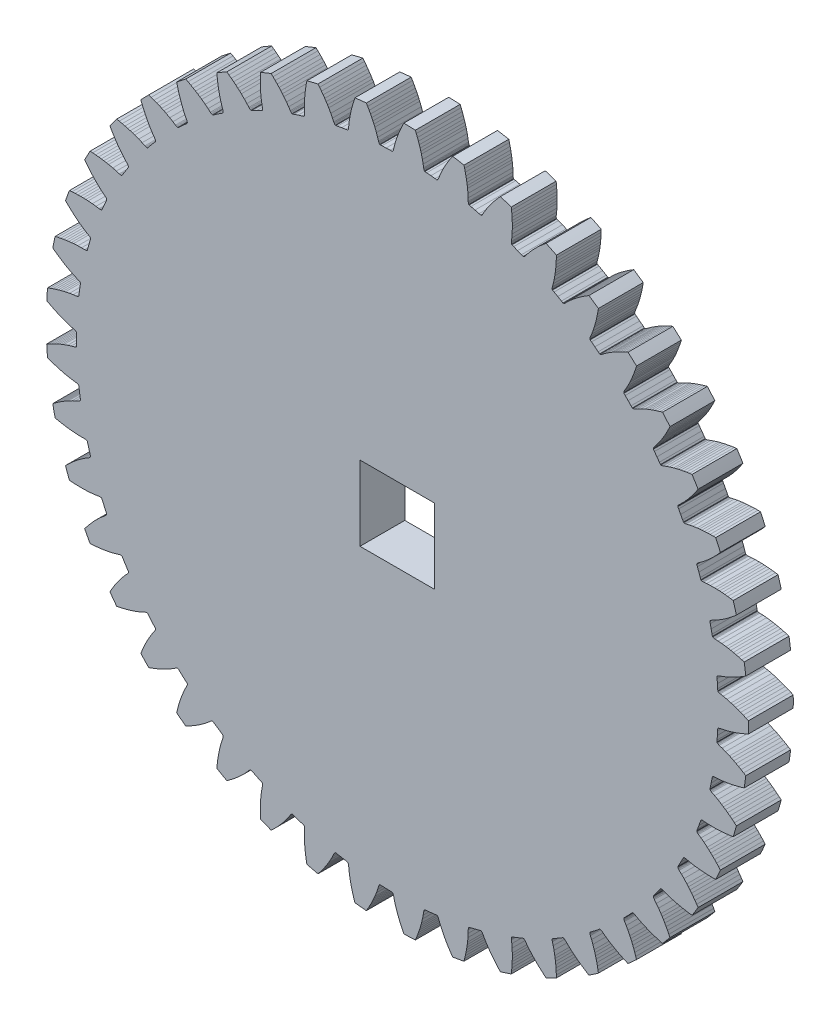
SolidWorks part; units mm, degrees
ref_plane "Front Plane" through (0, 0, 0) normal (0, 0, 1) x (1, 0, 0)
ref_plane "Top Plane" through (0, 0, 0) normal (0, 1, 0) x (1, 0, 0)
ref_plane "Right Plane" through (0, 0, 0) normal (1, 0, 0) x (0, 0, -1)
sketch "Model" plane through (0, 0, 0) normal (0, 0, 1) x (1, 0, 0)
  line L0 (46.3495, 5.592) -> (46.0028, 5.3808)
  line L1 (46.0028, 5.3808) -> (45.6677, 5.1861)
  line L2 (45.6677, 5.1861) -> (45.3461, 5.0082)
  line L3 (45.3461, 5.0082) -> (45.0376, 4.8458)
  line L4 (45.0376, 4.8458) -> (44.7407, 4.6975)
  line L5 (44.7407, 4.6975) -> (44.4596, 4.5643)
  line L6 (44.4596, 4.5643) -> (43.938, 4.3367)
  line L7 (43.938, 4.3367) -> (43.4773, 4.1581)
  line L8 (43.4773, 4.1581) -> (43.0884, 4.0249)
  line L9 (43.0884, 4.0249) -> (42.9864, 3.984)
  line L10 (42.9864, 3.984) -> (42.9051, 3.9409)
  line L11 (42.9051, 3.9409) -> (42.8444, 3.8966)
  line L12 (42.8444, 3.8966) -> (42.8043, 3.852)
  line L13 (42.8043, 3.852) -> (42.7849, 3.8077)
  line L14 (42.7849, 3.8077) -> (42.783, 3.786)
  line L15 (42.783, 3.786) -> (42.8026, 3.5571)
  line L16 (42.8026, 3.5571) -> (42.8454, 2.996)
  line L17 (42.8454, 2.996) -> (42.8811, 2.4345)
  line L18 (42.8811, 2.4345) -> (42.8935, 2.2051)
  line L19 (42.8935, 2.2051) -> (42.8985, 2.1839)
  line L20 (42.8985, 2.1839) -> (42.9239, 2.1427)
  line L21 (42.9239, 2.1427) -> (42.9697, 2.1041)
  line L22 (42.9697, 2.1041) -> (43.036, 2.0686)
  line L23 (43.036, 2.0686) -> (43.1225, 2.0373)
  line L24 (43.1225, 2.0373) -> (43.2292, 2.011)
  line L25 (43.2292, 2.011) -> (43.6329, 1.9332)
  line L26 (43.6329, 1.9332) -> (44.1139, 1.8205)
  line L27 (44.1139, 1.8205) -> (44.6621, 1.6677)
  line L28 (44.6621, 1.6677) -> (44.9591, 1.5749)
  line L29 (44.9591, 1.5749) -> (45.2737, 1.4693)
  line L30 (45.2737, 1.4693) -> (45.6018, 1.3515)
  line L31 (45.6018, 1.3515) -> (45.945, 1.2201)
  line L32 (45.945, 1.2201) -> (46.3039, 1.0739)
  line L33 (46.3039, 1.0739) -> (46.6767, 0.913)
  line L34 (46.6767, 0.913) -> (46.9937, 0.7687)
  line L35 (46.9937, -0.7687) -> (46.6767, -0.913)
  line L36 (46.6767, -0.913) -> (46.3039, -1.0739)
  line L37 (46.3039, -1.0739) -> (45.945, -1.2201)
  line L38 (45.945, -1.2201) -> (45.6018, -1.3515)
  line L39 (45.6018, -1.3515) -> (45.2737, -1.4693)
  line L40 (45.2737, -1.4693) -> (44.9591, -1.5749)
  line L41 (44.9591, -1.5749) -> (44.6621, -1.6677)
  line L42 (44.6621, -1.6677) -> (44.1139, -1.8205)
  line L43 (44.1139, -1.8205) -> (43.6329, -1.9332)
  line L44 (43.6329, -1.9332) -> (43.2292, -2.011)
  line L45 (43.2292, -2.011) -> (43.1225, -2.0373)
  line L46 (43.1225, -2.0373) -> (43.036, -2.0686)
  line L47 (43.036, -2.0686) -> (42.9697, -2.1041)
  line L48 (42.9697, -2.1041) -> (42.9239, -2.1427)
  line L49 (42.9239, -2.1427) -> (42.8985, -2.1839)
  line L50 (42.8985, -2.1839) -> (42.8935, -2.2051)
  line L51 (42.8935, -2.2051) -> (42.8811, -2.4345)
  line L52 (42.8811, -2.4345) -> (42.8454, -2.996)
  line L53 (42.8454, -2.996) -> (42.8026, -3.5571)
  line L54 (42.8026, -3.5571) -> (42.783, -3.786)
  line L55 (42.783, -3.786) -> (42.7849, -3.8077)
  line L56 (42.7849, -3.8077) -> (42.8043, -3.852)
  line L57 (42.8043, -3.852) -> (42.8444, -3.8966)
  line L58 (42.8444, -3.8966) -> (42.9051, -3.9409)
  line L59 (42.9051, -3.9409) -> (42.9864, -3.984)
  line L60 (42.9864, -3.984) -> (43.0884, -4.0249)
  line L61 (43.0884, -4.0249) -> (43.4773, -4.1581)
  line L62 (43.4773, -4.1581) -> (43.938, -4.3367)
  line L63 (43.938, -4.3367) -> (44.4596, -4.5643)
  line L64 (44.4596, -4.5643) -> (44.7407, -4.6975)
  line L65 (44.7407, -4.6975) -> (45.0376, -4.8458)
  line L66 (45.0376, -4.8458) -> (45.3461, -5.0082)
  line L67 (45.3461, -5.0082) -> (45.6677, -5.1861)
  line L68 (45.6677, -5.1861) -> (46.0028, -5.3808)
  line L69 (46.0028, -5.3808) -> (46.3495, -5.592)
  line L70 (46.3495, -5.592) -> (46.6434, -5.779)
  line L71 (46.4294, -7.3015) -> (46.0953, -7.4002)
  line L72 (46.0953, -7.4002) -> (45.7038, -7.5078)
  line L73 (45.7038, -7.5078) -> (45.3281, -7.6025)
  line L74 (45.3281, -7.6025) -> (44.9699, -7.6849)
  line L75 (44.9699, -7.6849) -> (44.6286, -7.7559)
  line L76 (44.6286, -7.7559) -> (44.3024, -7.8167)
  line L77 (44.3024, -7.8167) -> (43.9954, -7.8673)
  line L78 (43.9954, -7.8673) -> (43.4313, -7.9423)
  line L79 (43.4313, -7.9423) -> (42.9392, -7.9869)
  line L80 (42.9392, -7.9869) -> (42.5286, -8.0078)
  line L81 (42.5286, -8.0078) -> (42.4193, -8.019)
  line L82 (42.4193, -8.019) -> (42.3293, -8.038)
  line L83 (42.3293, -8.038) -> (42.2587, -8.0638)
  line L84 (42.2587, -8.0638) -> (42.2079, -8.0957)
  line L85 (42.2079, -8.0957) -> (42.1771, -8.1329)
  line L86 (42.1771, -8.1329) -> (42.1692, -8.1532)
  line L87 (42.1692, -8.1532) -> (42.125, -8.3787)
  line L88 (42.125, -8.3787) -> (42.0114, -8.9298)
  line L89 (42.0114, -8.9298) -> (41.891, -9.4794)
  line L90 (41.891, -9.4794) -> (41.8397, -9.7034)
  line L91 (41.8397, -9.7034) -> (41.8386, -9.7252)
  line L92 (41.8386, -9.7252) -> (41.8517, -9.7717)
  line L93 (41.8517, -9.7717) -> (41.8851, -9.8215)
  line L94 (41.8851, -9.8215) -> (41.939, -9.8738)
  line L95 (41.939, -9.8738) -> (42.0136, -9.9278)
  line L96 (42.0136, -9.9278) -> (42.1089, -9.9825)
  line L97 (42.1089, -9.9825) -> (42.4755, -10.1685)
  line L98 (42.4755, -10.1685) -> (42.9068, -10.4094)
  line L99 (42.9068, -10.4094) -> (43.3917, -10.7074)
  line L100 (43.3917, -10.7074) -> (43.6515, -10.8785)
  line L101 (43.6515, -10.8785) -> (43.9248, -11.0667)
  line L102 (43.9248, -11.0667) -> (44.2078, -11.2704)
  line L103 (44.2078, -11.2704) -> (44.5015, -11.4913)
  line L104 (44.5015, -11.4913) -> (44.8062, -11.7308)
  line L105 (44.8062, -11.7308) -> (45.1201, -11.9882)
  line L106 (45.1201, -11.9882) -> (45.3851, -12.2143)
  line L107 (44.9614, -13.6921) -> (44.6168, -13.7434)
  line L108 (44.6168, -13.7434) -> (44.2142, -13.7954)
  line L109 (44.2142, -13.7954) -> (43.8289, -13.837)
  line L110 (43.8289, -13.837) -> (43.4627, -13.8687)
  line L111 (43.4627, -13.8687) -> (43.1148, -13.8915)
  line L112 (43.1148, -13.8915) -> (42.7833, -13.9063)
  line L113 (42.7833, -13.9063) -> (42.4723, -13.9137)
  line L114 (42.4723, -13.9137) -> (41.9032, -13.9095)
  line L115 (41.9032, -13.9095) -> (41.4097, -13.8852)
  line L116 (41.4097, -13.8852) -> (41.0003, -13.8487)
  line L117 (41.0003, -13.8487) -> (40.8905, -13.8446)
  line L118 (40.8905, -13.8446) -> (40.7986, -13.8508)
  line L119 (40.7986, -13.8508) -> (40.7252, -13.8666)
  line L120 (40.7252, -13.8666) -> (40.6704, -13.8911)
  line L121 (40.6704, -13.8911) -> (40.6347, -13.9237)
  line L122 (40.6347, -13.9237) -> (40.6241, -13.9427)
  line L123 (40.6241, -13.9427) -> (40.5489, -14.1599)
  line L124 (40.5489, -14.1599) -> (40.3598, -14.6898)
  line L125 (40.3598, -14.6898) -> (40.164, -15.2173)
  line L126 (40.164, -15.2173) -> (40.0821, -15.4319)
  line L127 (40.0821, -15.4319) -> (40.078, -15.4533)
  line L128 (40.078, -15.4533) -> (40.0844, -15.5012)
  line L129 (40.0844, -15.5012) -> (40.1106, -15.5552)
  line L130 (40.1106, -15.5552) -> (40.1567, -15.6145)
  line L131 (40.1567, -15.6145) -> (40.2231, -15.6783)
  line L132 (40.2231, -15.6783) -> (40.3098, -15.7458)
  line L133 (40.3098, -15.7458) -> (40.6469, -15.981)
  line L134 (40.6469, -15.981) -> (41.0406, -16.2796)
  line L135 (41.0406, -16.2796) -> (41.4792, -16.6422)
  line L136 (41.4792, -16.6422) -> (41.7127, -16.8477)
  line L137 (41.7127, -16.8477) -> (41.9572, -17.0722)
  line L138 (41.9572, -17.0722) -> (42.209, -17.3133)
  line L139 (42.209, -17.3133) -> (42.4691, -17.5729)
  line L140 (42.4691, -17.5729) -> (42.7376, -17.8524)
  line L141 (42.7376, -17.8524) -> (43.0126, -18.1511)
  line L142 (43.0126, -18.1511) -> (43.2435, -18.4118)
  line L143 (42.6182, -19.8163) -> (42.2699, -19.8192)
  line L144 (42.2699, -19.8192) -> (41.8639, -19.8146)
  line L145 (41.8639, -19.8146) -> (41.4766, -19.8021)
  line L146 (41.4766, -19.8021) -> (41.1096, -19.7826)
  line L147 (41.1096, -19.7826) -> (40.7619, -19.7568)
  line L148 (40.7619, -19.7568) -> (40.4316, -19.7253)
  line L149 (40.4316, -19.7253) -> (40.1226, -19.6893)
  line L150 (40.1226, -19.6893) -> (39.5596, -19.6059)
  line L151 (39.5596, -19.6059) -> (39.0743, -19.5131)
  line L152 (39.0743, -19.5131) -> (38.6739, -19.42)
  line L153 (38.6739, -19.42) -> (38.5657, -19.4007)
  line L154 (38.5657, -19.4007) -> (38.4739, -19.3941)
  line L155 (38.4739, -19.3941) -> (38.399, -19.3995)
  line L156 (38.399, -19.3995) -> (38.3414, -19.4162)
  line L157 (38.3414, -19.4162) -> (38.3015, -19.4434)
  line L158 (38.3015, -19.4434) -> (38.2883, -19.4608)
  line L159 (38.2883, -19.4608) -> (38.1836, -19.6654)
  line L160 (38.1836, -19.6654) -> (37.9226, -20.1638)
  line L161 (37.9226, -20.1638) -> (37.6553, -20.6589)
  line L162 (37.6553, -20.6589) -> (37.5443, -20.8601)
  line L163 (37.5443, -20.8601) -> (37.5373, -20.8807)
  line L164 (37.5373, -20.8807) -> (37.537, -20.929)
  line L165 (37.537, -20.929) -> (37.5554, -20.9861)
  line L166 (37.5554, -20.9861) -> (37.5928, -21.0513)
  line L167 (37.5928, -21.0513) -> (37.6496, -21.1237)
  line L168 (37.6496, -21.1237) -> (37.7261, -21.2026)
  line L169 (37.7261, -21.2026) -> (38.0272, -21.4824)
  line L170 (38.0272, -21.4824) -> (38.3755, -21.8329)
  line L171 (38.3755, -21.8329) -> (38.7594, -22.253)
  line L172 (38.7594, -22.253) -> (38.962, -22.4891)
  line L173 (38.962, -22.4891) -> (39.1729, -22.7453)
  line L174 (39.1729, -22.7453) -> (39.3887, -23.0191)
  line L175 (39.3887, -23.0191) -> (39.6101, -23.3125)
  line L176 (39.6101, -23.3125) -> (39.8371, -23.6266)
  line L177 (39.8371, -23.6266) -> (40.0679, -23.9606)
  line L178 (40.0679, -23.9606) -> (40.2603, -24.251)
  line L179 (39.4456, -25.5548) -> (39.1002, -25.5091)
  line L180 (39.1002, -25.5091) -> (38.6989, -25.4481)
  line L181 (38.6989, -25.4481) -> (38.317, -25.3818)
  line L182 (38.317, -25.3818) -> (37.9563, -25.3114)
  line L183 (37.9563, -25.3114) -> (37.6156, -25.2375)
  line L184 (37.6156, -25.2375) -> (37.2929, -25.1603)
  line L185 (37.2929, -25.1603) -> (36.9919, -25.0816)
  line L186 (36.9919, -25.0816) -> (36.446, -24.9207)
  line L187 (36.446, -24.9207) -> (35.9783, -24.7613)
  line L188 (35.9783, -24.7613) -> (35.5948, -24.6134)
  line L189 (35.5948, -24.6134) -> (35.4903, -24.5792)
  line L190 (35.4903, -24.5792) -> (35.4004, -24.5599)
  line L191 (35.4004, -24.5599) -> (35.3254, -24.5548)
  line L192 (35.3254, -24.5548) -> (35.266, -24.5633)
  line L193 (35.266, -24.5633) -> (35.2227, -24.5848)
  line L194 (35.2227, -24.5848) -> (35.2073, -24.6001)
  line L195 (35.2073, -24.6001) -> (35.0751, -24.7881)
  line L196 (35.0751, -24.7881) -> (34.7473, -25.2454)
  line L197 (34.7473, -25.2454) -> (34.4137, -25.6985)
  line L198 (34.4137, -25.6985) -> (34.2757, -25.8822)
  line L199 (34.2757, -25.8822) -> (34.2659, -25.9017)
  line L200 (34.2659, -25.9017) -> (34.2589, -25.9495)
  line L201 (34.2589, -25.9495) -> (34.2692, -26.0086)
  line L202 (34.2692, -26.0086) -> (34.2972, -26.0783)
  line L203 (34.2972, -26.0783) -> (34.3434, -26.1579)
  line L204 (34.3434, -26.1579) -> (34.4081, -26.2467)
  line L205 (34.4081, -26.2467) -> (34.6673, -26.5657)
  line L206 (34.6673, -26.5657) -> (34.9635, -26.9613)
  line L207 (34.9635, -26.9613) -> (35.2852, -27.4307)
  line L208 (35.2852, -27.4307) -> (35.453, -27.6927)
  line L209 (35.453, -27.6927) -> (35.6261, -27.9758)
  line L210 (35.6261, -27.9758) -> (35.8017, -28.277)
  line L211 (35.8017, -28.277) -> (35.9802, -28.5982)
  line L212 (35.9802, -28.5982) -> (36.1612, -28.9409)
  line L213 (36.1612, -28.9409) -> (36.3433, -29.3038)
  line L214 (36.3433, -29.3038) -> (36.4934, -29.6181)
  line L215 (35.5052, -30.7958) -> (35.1695, -30.7026)
  line L216 (35.1695, -30.7026) -> (34.7806, -30.5863)
  line L217 (34.7806, -30.5863) -> (34.4117, -30.4675)
  line L218 (34.4117, -30.4675) -> (34.0643, -30.3476)
  line L219 (34.0643, -30.3476) -> (33.7372, -30.2269)
  line L220 (33.7372, -30.2269) -> (33.4283, -30.1056)
  line L221 (33.4283, -30.1056) -> (33.1412, -29.9858)
  line L222 (33.1412, -29.9858) -> (32.623, -29.7505)
  line L223 (32.623, -29.7505) -> (32.1821, -29.5276)
  line L224 (32.1821, -29.5276) -> (31.8228, -29.3277)
  line L225 (31.8228, -29.3277) -> (31.7242, -29.2793)
  line L226 (31.7242, -29.2793) -> (31.6378, -29.2477)
  line L227 (31.6378, -29.2477) -> (31.5642, -29.2322)
  line L228 (31.5642, -29.2322) -> (31.5043, -29.2324)
  line L229 (31.5043, -29.2324) -> (31.4584, -29.2475)
  line L230 (31.4584, -29.2475) -> (31.441, -29.2606)
  line L231 (31.441, -29.2606) -> (31.2839, -29.4284)
  line L232 (31.2839, -29.4284) -> (30.8956, -29.8356)
  line L233 (30.8956, -29.8356) -> (30.5023, -30.2378)
  line L234 (30.5023, -30.2378) -> (30.34, -30.4006)
  line L235 (30.34, -30.4006) -> (30.3276, -30.4185)
  line L236 (30.3276, -30.4185) -> (30.314, -30.4649)
  line L237 (30.314, -30.4649) -> (30.316, -30.5248)
  line L238 (30.316, -30.5248) -> (30.334, -30.5978)
  line L239 (30.334, -30.5978) -> (30.3686, -30.683)
  line L240 (30.3686, -30.683) -> (30.4204, -30.7799)
  line L241 (30.4204, -30.7799) -> (30.6327, -31.132)
  line L242 (30.6327, -31.132) -> (30.8709, -31.5649)
  line L243 (30.8709, -31.5649) -> (31.1241, -32.0745)
  line L244 (31.1241, -32.0745) -> (31.2539, -32.3573)
  line L245 (31.2539, -32.3573) -> (31.3859, -32.6617)
  line L246 (31.3859, -32.6617) -> (31.5179, -32.9844)
  line L247 (31.5179, -32.9844) -> (31.6499, -33.3274)
  line L248 (31.6499, -33.3274) -> (31.7815, -33.6919)
  line L249 (31.7815, -33.6919) -> (31.9113, -34.0766)
  line L250 (31.9113, -34.0766) -> (32.0162, -34.4088)
  line L251 (30.8737, -35.4375) -> (30.5543, -35.2984)
  line L252 (30.5543, -35.2984) -> (30.1853, -35.1291)
  line L253 (30.1853, -35.1291) -> (29.8365, -34.9602)
  line L254 (29.8365, -34.9602) -> (29.5092, -34.7931)
  line L255 (29.5092, -34.7931) -> (29.2021, -34.6281)
  line L256 (29.2021, -34.6281) -> (28.9131, -34.4649)
  line L257 (28.9131, -34.4649) -> (28.6454, -34.3063)
  line L258 (28.6454, -34.3063) -> (28.1651, -34.0012)
  line L259 (28.1651, -34.0012) -> (27.7594, -33.7191)
  line L260 (27.7594, -33.7191) -> (27.4315, -33.4712)
  line L261 (27.4315, -33.4712) -> (27.3406, -33.4095)
  line L262 (27.3406, -33.4095) -> (27.2594, -33.3662)
  line L263 (27.2594, -33.3662) -> (27.1887, -33.3406)
  line L264 (27.1887, -33.3406) -> (27.1293, -33.3324)
  line L265 (27.1293, -33.3324) -> (27.0818, -33.3411)
  line L266 (27.0818, -33.3411) -> (27.0627, -33.3516)
  line L267 (27.0627, -33.3516) -> (26.8838, -33.4959)
  line L268 (26.8838, -33.4959) -> (26.4427, -33.8451)
  line L269 (26.4427, -33.8451) -> (25.9971, -34.1887)
  line L270 (25.9971, -34.1887) -> (25.8138, -34.3273)
  line L271 (25.8138, -34.3273) -> (25.799, -34.3433)
  line L272 (25.799, -34.3433) -> (25.7791, -34.3873)
  line L273 (25.7791, -34.3873) -> (25.7727, -34.4469)
  line L274 (25.7727, -34.4469) -> (25.7804, -34.5217)
  line L275 (25.7804, -34.5217) -> (25.8028, -34.6109)
  line L276 (25.8028, -34.6109) -> (25.8406, -34.7141)
  line L277 (25.8406, -34.7141) -> (26.0019, -35.0922)
  line L278 (26.0019, -35.0922) -> (26.1775, -35.5541)
  line L279 (26.1775, -35.5541) -> (26.3573, -36.094)
  line L280 (26.3573, -36.094) -> (26.4465, -36.3921)
  line L281 (26.4465, -36.3921) -> (26.5348, -36.7119)
  line L282 (26.5348, -36.7119) -> (26.6206, -37.0499)
  line L283 (26.6206, -37.0499) -> (26.7036, -37.4079)
  line L284 (26.7036, -37.4079) -> (26.7832, -37.7872)
  line L285 (26.7832, -37.7872) -> (26.8582, -38.1862)
  line L286 (26.8582, -38.1862) -> (26.9158, -38.5297)
  line L287 (25.6413, -39.3894) -> (25.3444, -39.2072)
  line L288 (25.3444, -39.2072) -> (25.0025, -38.9882)
  line L289 (25.0025, -38.9882) -> (24.6806, -38.7724)
  line L290 (24.6806, -38.7724) -> (24.3798, -38.5613)
  line L291 (24.3798, -38.5613) -> (24.0986, -38.3552)
  line L292 (24.0986, -38.3552) -> (23.8351, -38.1534)
  line L293 (23.8351, -38.1534) -> (23.5921, -37.9592)
  line L294 (23.5921, -37.9592) -> (23.1589, -37.5901)
  line L295 (23.1589, -37.5901) -> (22.7965, -37.2543)
  line L296 (22.7965, -37.2543) -> (22.5063, -36.9632)
  line L297 (22.5063, -36.9632) -> (22.4248, -36.8895)
  line L298 (22.4248, -36.8895) -> (22.3504, -36.8352)
  line L299 (22.3504, -36.8352) -> (22.284, -36.8001)
  line L300 (22.284, -36.8001) -> (22.2263, -36.7837)
  line L301 (22.2263, -36.7837) -> (22.178, -36.7857)
  line L302 (22.178, -36.7857) -> (22.1577, -36.7934)
  line L303 (22.1577, -36.7934) -> (21.9605, -36.9114)
  line L304 (21.9605, -36.9114) -> (21.475, -37.1958)
  line L305 (21.475, -37.1958) -> (20.986, -37.474)
  line L306 (20.986, -37.474) -> (20.7852, -37.5858)
  line L307 (20.7852, -37.5858) -> (20.7683, -37.5996)
  line L308 (20.7683, -37.5996) -> (20.7425, -37.6404)
  line L309 (20.7425, -37.6404) -> (20.7278, -37.6986)
  line L310 (20.7278, -37.6986) -> (20.725, -37.7736)
  line L311 (20.725, -37.7736) -> (20.7348, -37.8652)
  line L312 (20.7348, -37.8652) -> (20.7579, -37.9726)
  line L313 (20.7579, -37.9726) -> (20.8649, -38.3695)
  line L314 (20.8649, -38.3695) -> (20.9746, -38.8513)
  line L315 (20.9746, -38.8513) -> (21.0775, -39.411)
  line L316 (21.0775, -39.411) -> (21.1243, -39.7185)
  line L317 (21.1243, -39.7185) -> (21.1673, -40.0476)
  line L318 (21.1673, -40.0476) -> (21.2052, -40.3942)
  line L319 (21.2052, -40.3942) -> (21.2376, -40.7602)
  line L320 (21.2376, -40.7602) -> (21.2636, -41.1469)
  line L321 (21.2636, -41.1469) -> (21.2823, -41.5525)
  line L322 (21.2823, -41.5525) -> (21.2916, -41.9007)
  line L323 (19.9098, -42.5746) -> (19.6411, -42.3529)
  line L324 (19.6411, -42.3529) -> (19.3331, -42.0885)
  line L325 (19.3331, -42.0885) -> (19.0444, -41.8299)
  line L326 (19.0444, -41.8299) -> (18.7758, -41.5791)
  line L327 (18.7758, -41.5791) -> (18.526, -41.3358)
  line L328 (18.526, -41.3358) -> (18.2932, -41.0994)
  line L329 (18.2932, -41.0994) -> (18.0797, -40.8731)
  line L330 (18.0797, -40.8731) -> (17.702, -40.4474)
  line L331 (17.702, -40.4474) -> (17.3898, -40.0644)
  line L332 (17.3898, -40.0644) -> (17.143, -39.7357)
  line L333 (17.143, -39.7357) -> (17.0725, -39.6514)
  line L334 (17.0725, -39.6514) -> (17.0064, -39.5873)
  line L335 (17.0064, -39.5873) -> (16.9456, -39.5433)
  line L336 (16.9456, -39.5433) -> (16.8907, -39.519)
  line L337 (16.8907, -39.519) -> (16.8426, -39.5142)
  line L338 (16.8426, -39.5142) -> (16.8214, -39.5191)
  line L339 (16.8214, -39.5191) -> (16.6097, -39.6085)
  line L340 (16.6097, -39.6085) -> (16.0894, -39.8225)
  line L341 (16.0894, -39.8225) -> (15.5664, -40.03)
  line L342 (15.5664, -40.03) -> (15.352, -40.1128)
  line L343 (15.352, -40.1128) -> (15.3333, -40.124)
  line L344 (15.3333, -40.124) -> (15.3021, -40.1609)
  line L345 (15.3021, -40.1609) -> (15.2795, -40.2164)
  line L346 (15.2795, -40.2164) -> (15.2663, -40.2904)
  line L347 (15.2663, -40.2904) -> (15.2632, -40.3824)
  line L348 (15.2632, -40.3824) -> (15.2711, -40.492)
  line L349 (15.2711, -40.492) -> (15.3219, -40.8999)
  line L350 (15.3219, -40.8999) -> (15.3634, -41.3923)
  line L351 (15.3634, -41.3923) -> (15.3874, -41.9608)
  line L352 (15.3874, -41.9608) -> (15.391, -42.2719)
  line L353 (15.391, -42.2719) -> (15.3877, -42.6038)
  line L354 (15.3877, -42.6038) -> (15.3771, -42.9523)
  line L355 (15.3771, -42.9523) -> (15.3581, -43.3193)
  line L356 (15.3581, -43.3193) -> (15.3301, -43.7058)
  line L357 (15.3301, -43.7058) -> (15.2922, -44.11)
  line L358 (15.2922, -44.11) -> (15.2529, -44.4561)
  line L359 (13.7908, -44.9312) -> (13.5556, -44.6743)
  line L360 (13.5556, -44.6743) -> (13.2873, -44.3695)
  line L361 (13.2873, -44.3695) -> (13.0374, -44.0733)
  line L362 (13.0374, -44.0733) -> (12.8064, -43.7875)
  line L363 (12.8064, -43.7875) -> (12.5929, -43.5119)
  line L364 (12.5929, -43.5119) -> (12.3953, -43.2453)
  line L365 (12.3953, -43.2453) -> (12.2153, -42.9916)
  line L366 (12.2153, -42.9916) -> (11.9005, -42.5174)
  line L367 (11.9005, -42.5174) -> (11.6447, -42.0947)
  line L368 (11.6447, -42.0947) -> (11.446, -41.7348)
  line L369 (11.446, -41.7348) -> (11.388, -41.6415)
  line L370 (11.388, -41.6415) -> (11.3314, -41.5689)
  line L371 (11.3314, -41.5689) -> (11.2773, -41.5168)
  line L372 (11.2773, -41.5168) -> (11.2263, -41.4851)
  line L373 (11.2263, -41.4851) -> (11.1794, -41.4737)
  line L374 (11.1794, -41.4737) -> (11.1577, -41.4756)
  line L375 (11.1577, -41.4756) -> (10.9356, -41.5347)
  line L376 (10.9356, -41.5347) -> (10.3905, -41.6742)
  line L377 (10.3905, -41.6742) -> (9.8438, -41.8069)
  line L378 (9.8438, -41.8069) -> (9.6199, -41.859)
  line L379 (9.6199, -41.859) -> (9.5999, -41.8675)
  line L380 (9.5999, -41.8675) -> (9.5638, -41.8997)
  line L381 (9.5638, -41.8997) -> (9.5337, -41.9515)
  line L382 (9.5337, -41.9515) -> (9.5103, -42.023)
  line L383 (9.5103, -42.023) -> (9.4945, -42.1136)
  line L384 (9.4945, -42.1136) -> (9.4871, -42.2232)
  line L385 (9.4871, -42.2232) -> (9.4806, -42.6343)
  line L386 (9.4806, -42.6343) -> (9.4532, -43.1276)
  line L387 (9.4532, -43.1276) -> (9.3979, -43.694)
  line L388 (9.3979, -43.694) -> (9.3581, -44.0026)
  line L389 (9.3581, -44.0026) -> (9.3087, -44.3307)
  line L390 (9.3087, -44.3307) -> (9.2496, -44.6743)
  line L391 (9.2496, -44.6743) -> (9.1798, -45.0351)
  line L392 (9.1798, -45.0351) -> (9.0982, -45.414)
  line L393 (9.0982, -45.414) -> (9.0044, -45.809)
  line L394 (9.0044, -45.809) -> (8.9174, -46.1463)
  line L395 (7.4034, -46.4133) -> (7.2062, -46.1261)
  line L396 (7.2062, -46.1261) -> (6.983, -45.787)
  line L397 (6.983, -45.787) -> (6.7767, -45.4589)
  line L398 (6.7767, -45.4589) -> (6.5877, -45.1437)
  line L399 (6.5877, -45.1437) -> (6.4147, -44.841)
  line L400 (6.4147, -44.841) -> (6.2561, -44.5495)
  line L401 (6.2561, -44.5495) -> (6.1131, -44.2732)
  line L402 (6.1131, -44.2732) -> (5.8674, -43.7599)
  line L403 (5.8674, -43.7599) -> (5.6729, -43.3057)
  line L404 (5.6729, -43.3057) -> (5.5262, -42.9217)
  line L405 (5.5262, -42.9217) -> (5.4818, -42.8212)
  line L406 (5.4818, -42.8212) -> (5.4359, -42.7414)
  line L407 (5.4359, -42.7414) -> (5.3895, -42.6823)
  line L408 (5.3895, -42.6823) -> (5.3435, -42.6438)
  line L409 (5.3435, -42.6438) -> (5.2986, -42.626)
  line L410 (5.2986, -42.626) -> (5.2768, -42.6248)
  line L411 (5.2768, -42.6248) -> (5.0487, -42.6524)
  line L412 (5.0487, -42.6524) -> (4.4895, -42.7147)
  line L413 (4.4895, -42.7147) -> (3.9296, -42.77)
  line L414 (3.9296, -42.77) -> (3.7007, -42.7904)
  line L415 (3.7007, -42.7904) -> (3.6797, -42.7961)
  line L416 (3.6797, -42.7961) -> (3.6395, -42.8229)
  line L417 (3.6395, -42.8229) -> (3.6024, -42.8701)
  line L418 (3.6024, -42.8701) -> (3.5693, -42.9376)
  line L419 (3.5693, -42.9376) -> (3.5411, -43.0252)
  line L420 (3.5411, -43.0252) -> (3.5184, -43.1327)
  line L421 (3.5184, -43.1327) -> (3.4548, -43.5388)
  line L422 (3.4548, -43.5388) -> (3.359, -44.0235)
  line L423 (3.359, -44.0235) -> (3.2254, -44.5767)
  line L424 (3.2254, -44.5767) -> (3.143, -44.8767)
  line L425 (3.143, -44.8767) -> (3.0485, -45.1948)
  line L426 (3.0485, -45.1948) -> (2.9421, -45.5269)
  line L427 (2.9421, -45.5269) -> (2.8228, -45.8744)
  line L428 (2.8228, -45.8744) -> (2.6893, -46.2383)
  line L429 (2.6893, -46.2383) -> (2.5414, -46.6164)
  line L430 (2.5414, -46.6164) -> (2.4083, -46.9383)
  line L431 (0.8718, -46.9919) -> (0.7166, -46.6801)
  line L432 (0.7166, -46.6801) -> (0.5427, -46.3132)
  line L433 (0.5427, -46.3132) -> (0.3841, -45.9596)
  line L434 (0.3841, -45.9596) -> (0.2408, -45.6212)
  line L435 (0.2408, -45.6212) -> (0.1116, -45.2974)
  line L436 (0.1116, -45.2974) -> (-0.0049, -44.9867)
  line L437 (-0.0049, -44.9867) -> (-0.108, -44.6931)
  line L438 (-0.108, -44.6931) -> (-0.2799, -44.1506)
  line L439 (-0.2799, -44.1506) -> (-0.4093, -43.6737)
  line L440 (-0.4093, -43.6737) -> (-0.5011, -43.273)
  line L441 (-0.5011, -43.273) -> (-0.5312, -43.1674)
  line L442 (-0.5312, -43.1674) -> (-0.5655, -43.082)
  line L443 (-0.5655, -43.082) -> (-0.6032, -43.017)
  line L444 (-0.6032, -43.017) -> (-0.6434, -42.9725)
  line L445 (-0.6434, -42.9725) -> (-0.6854, -42.9486)
  line L446 (-0.6854, -42.9486) -> (-0.7068, -42.9443)
  line L447 (-0.7068, -42.9443) -> (-0.9365, -42.9399)
  line L448 (-0.9365, -42.9399) -> (-1.4989, -42.9238)
  line L449 (-1.4989, -42.9238) -> (-2.0611, -42.9007)
  line L450 (-2.0611, -42.9007) -> (-2.2906, -42.889)
  line L451 (-2.2906, -42.889) -> (-2.3122, -42.8918)
  line L452 (-2.3122, -42.8918) -> (-2.3558, -42.9127)
  line L453 (-2.3558, -42.9127) -> (-2.399, -42.9543)
  line L454 (-2.399, -42.9543) -> (-2.4412, -43.0165)
  line L455 (-2.4412, -43.0165) -> (-2.4813, -43.0993)
  line L456 (-2.4813, -43.0993) -> (-2.5187, -43.2026)
  line L457 (-2.5187, -43.2026) -> (-2.6383, -43.5959)
  line L458 (-2.6383, -43.5959) -> (-2.8006, -44.0626)
  line L459 (-2.8006, -44.0626) -> (-3.0099, -44.5918)
  line L460 (-3.0099, -44.5918) -> (-3.1332, -44.8774)
  line L461 (-3.1332, -44.8774) -> (-3.2711, -45.1792)
  line L462 (-3.2711, -45.1792) -> (-3.4226, -45.4933)
  line L463 (-3.4226, -45.4933) -> (-3.5892, -45.8208)
  line L464 (-3.5892, -45.8208) -> (-3.772, -46.1625)
  line L465 (-3.772, -46.1625) -> (-3.9711, -46.5164)
  line L466 (-3.9711, -46.5164) -> (-4.1477, -46.8166)
  line L467 (-5.6767, -46.6559) -> (-5.787, -46.3255)
  line L468 (-5.787, -46.3255) -> (-5.9081, -45.938)
  line L469 (-5.9081, -45.938) -> (-6.016, -45.5658)
  line L470 (-6.016, -45.5658) -> (-6.1108, -45.2107)
  line L471 (-6.1108, -45.2107) -> (-6.1937, -44.8721)
  line L472 (-6.1937, -44.8721) -> (-6.2658, -44.5482)
  line L473 (-6.2658, -44.5482) -> (-6.327, -44.2431)
  line L474 (-6.327, -44.2431) -> (-6.4217, -43.682)
  line L475 (-6.4217, -43.682) -> (-6.4835, -43.1918)
  line L476 (-6.4835, -43.1918) -> (-6.5186, -42.7822)
  line L477 (-6.5186, -42.7822) -> (-6.5337, -42.6733)
  line L478 (-6.5337, -42.6733) -> (-6.5558, -42.584)
  line L479 (-6.5558, -42.584) -> (-6.5841, -42.5144)
  line L480 (-6.5841, -42.5144) -> (-6.6178, -42.4647)
  line L481 (-6.6178, -42.4647) -> (-6.656, -42.4352)
  line L482 (-6.656, -42.4352) -> (-6.6766, -42.4281)
  line L483 (-6.6766, -42.4281) -> (-6.9035, -42.3917)
  line L484 (-6.9035, -42.3917) -> (-7.4582, -42.2975)
  line L485 (-7.4582, -42.2975) -> (-8.0117, -42.1963)
  line L486 (-8.0117, -42.1963) -> (-8.2373, -42.1529)
  line L487 (-8.2373, -42.1529) -> (-8.2591, -42.1525)
  line L488 (-8.2591, -42.1525) -> (-8.3051, -42.1672)
  line L489 (-8.3051, -42.1672) -> (-8.3538, -42.2023)
  line L490 (-8.3538, -42.2023) -> (-8.4041, -42.2581)
  line L491 (-8.4041, -42.2581) -> (-8.4555, -42.3345)
  line L492 (-8.4555, -42.3345) -> (-8.5068, -42.4316)
  line L493 (-8.5068, -42.4316) -> (-8.68, -42.8045)
  line L494 (-8.68, -42.8045) -> (-8.9057, -43.244)
  line L495 (-8.9057, -43.244) -> (-9.1866, -43.7389)
  line L496 (-9.1866, -43.7389) -> (-9.3484, -44.0046)
  line L497 (-9.3484, -44.0046) -> (-9.527, -44.2843)
  line L498 (-9.527, -44.2843) -> (-9.7207, -44.5742)
  line L499 (-9.7207, -44.5742) -> (-9.9313, -44.8754)
  line L500 (-9.9313, -44.8754) -> (-10.1599, -45.1883)
  line L501 (-10.1599, -45.1883) -> (-10.4062, -45.511)
  line L502 (-10.4062, -45.511) -> (-10.6229, -45.7838)
  line L503 (-12.1147, -45.4118) -> (-12.178, -45.0693)
  line L504 (-12.178, -45.0693) -> (-12.244, -44.6687)
  line L505 (-12.244, -44.6687) -> (-12.2989, -44.2851)
  line L506 (-12.2989, -44.2851) -> (-12.3434, -43.9203)
  line L507 (-12.3434, -43.9203) -> (-12.3784, -43.5734)
  line L508 (-12.3784, -43.5734) -> (-12.4047, -43.2426)
  line L509 (-12.4047, -43.2426) -> (-12.4229, -42.932)
  line L510 (-12.4229, -42.932) -> (-12.4386, -42.3631)
  line L511 (-12.4386, -42.3631) -> (-12.4315, -41.8691)
  line L512 (-12.4315, -41.8691) -> (-12.4093, -41.4586)
  line L513 (-12.4093, -41.4586) -> (-12.4091, -41.3487)
  line L514 (-12.4091, -41.3487) -> (-12.4185, -41.2572)
  line L515 (-12.4185, -41.2572) -> (-12.4369, -41.1843)
  line L516 (-12.4369, -41.1843) -> (-12.4633, -41.1305)
  line L517 (-12.4633, -41.1305) -> (-12.4971, -41.0959)
  line L518 (-12.4971, -41.0959) -> (-12.5164, -41.0859)
  line L519 (-12.5164, -41.0859) -> (-12.7361, -41.0184)
  line L520 (-12.7361, -41.0184) -> (-13.2723, -40.8479)
  line L521 (-13.2723, -40.8479) -> (-13.8063, -40.6706)
  line L522 (-13.8063, -40.6706) -> (-14.0237, -40.5962)
  line L523 (-14.0237, -40.5962) -> (-14.0452, -40.5929)
  line L524 (-14.0452, -40.5929) -> (-14.0928, -40.601)
  line L525 (-14.0928, -40.601) -> (-14.1459, -40.629)
  line L526 (-14.1459, -40.629) -> (-14.2035, -40.6772)
  line L527 (-14.2035, -40.6772) -> (-14.265, -40.7457)
  line L528 (-14.265, -40.7457) -> (-14.3294, -40.8347)
  line L529 (-14.3294, -40.8347) -> (-14.5527, -41.1799)
  line L530 (-14.5527, -41.1799) -> (-14.8374, -41.5837)
  line L531 (-14.8374, -41.5837) -> (-15.1844, -42.0347)
  line L532 (-15.1844, -42.0347) -> (-15.3817, -42.2753)
  line L533 (-15.3817, -42.2753) -> (-15.5975, -42.5274)
  line L534 (-15.5975, -42.5274) -> (-15.8297, -42.7875)
  line L535 (-15.8297, -42.7875) -> (-16.0801, -43.0565)
  line L536 (-16.0801, -43.0565) -> (-16.35, -43.3346)
  line L537 (-16.35, -43.3346) -> (-16.6389, -43.6199)
  line L538 (-16.6389, -43.6199) -> (-16.8914, -43.8598)
  line L539 (-18.3169, -43.2839) -> (-18.3319, -42.9358)
  line L540 (-18.3319, -42.9358) -> (-18.3415, -42.53)
  line L541 (-18.3415, -42.53) -> (-18.3425, -42.1424)
  line L542 (-18.3425, -42.1424) -> (-18.3358, -41.775)
  line L543 (-18.3358, -41.775) -> (-18.3222, -41.4266)
  line L544 (-18.3222, -41.4266) -> (-18.3022, -41.0954)
  line L545 (-18.3022, -41.0954) -> (-18.277, -40.7853)
  line L546 (-18.277, -40.7853) -> (-18.2133, -40.2197)
  line L547 (-18.2133, -40.2197) -> (-18.1376, -39.7315)
  line L548 (-18.1376, -39.7315) -> (-18.0585, -39.3281)
  line L549 (-18.0585, -39.3281) -> (-18.043, -39.2193)
  line L550 (-18.043, -39.2193) -> (-18.0396, -39.1273)
  line L551 (-18.0396, -39.1273) -> (-18.0476, -39.0526)
  line L552 (-18.0476, -39.0526) -> (-18.0663, -38.9956)
  line L553 (-18.0663, -38.9956) -> (-18.0949, -38.9567)
  line L554 (-18.0949, -38.9567) -> (-18.1127, -38.9441)
  line L555 (-18.1127, -38.9441) -> (-18.3208, -38.8467)
  line L556 (-18.3208, -38.8467) -> (-18.828, -38.6032)
  line L557 (-18.828, -38.6032) -> (-19.3322, -38.3534)
  line L558 (-19.3322, -38.3534) -> (-19.5371, -38.2494)
  line L559 (-19.5371, -38.2494) -> (-19.558, -38.2431)
  line L560 (-19.558, -38.2431) -> (-19.6063, -38.2445)
  line L561 (-19.6063, -38.2445) -> (-19.6627, -38.2649)
  line L562 (-19.6627, -38.2649) -> (-19.7265, -38.3046)
  line L563 (-19.7265, -38.3046) -> (-19.7969, -38.3639)
  line L564 (-19.7969, -38.3639) -> (-19.873, -38.4431)
  line L565 (-19.873, -38.4431) -> (-20.1422, -38.7538)
  line L566 (-20.1422, -38.7538) -> (-20.4803, -39.1141)
  line L567 (-20.4803, -39.1141) -> (-20.8868, -39.5124)
  line L568 (-20.8868, -39.5124) -> (-21.1156, -39.7232)
  line L569 (-21.1156, -39.7232) -> (-21.3644, -39.9428)
  line L570 (-21.3644, -39.9428) -> (-21.6305, -40.1681)
  line L571 (-21.6305, -40.1681) -> (-21.9159, -40.3996)
  line L572 (-21.9159, -40.3996) -> (-22.2219, -40.6374)
  line L573 (-22.2219, -40.6374) -> (-22.5477, -40.8797)
  line L574 (-22.5477, -40.8797) -> (-22.8311, -41.0821)
  line L575 (-24.1626, -40.3134) -> (-24.129, -39.9667)
  line L576 (-24.129, -39.9667) -> (-24.082, -39.5634)
  line L577 (-24.082, -39.5634) -> (-24.0291, -39.1795)
  line L578 (-24.0291, -39.1795) -> (-23.9713, -38.8166)
  line L579 (-23.9713, -38.8166) -> (-23.9093, -38.4735)
  line L580 (-23.9093, -38.4735) -> (-23.8435, -38.1482)
  line L581 (-23.8435, -38.1482) -> (-23.7753, -37.8447)
  line L582 (-23.7753, -37.8447) -> (-23.6336, -37.2935)
  line L583 (-23.6336, -37.2935) -> (-23.4906, -36.8206)
  line L584 (-23.4906, -36.8206) -> (-23.3562, -36.4321)
  line L585 (-23.3562, -36.4321) -> (-23.3257, -36.3265)
  line L586 (-23.3257, -36.3265) -> (-23.3095, -36.2359)
  line L587 (-23.3095, -36.2359) -> (-23.307, -36.1608)
  line L588 (-23.307, -36.1608) -> (-23.3176, -36.1018)
  line L589 (-23.3176, -36.1018) -> (-23.3405, -36.0593)
  line L590 (-23.3405, -36.0593) -> (-23.3564, -36.0443)
  line L591 (-23.3564, -36.0443) -> (-23.5489, -35.9188)
  line L592 (-23.5489, -35.9188) -> (-24.0173, -35.6072)
  line L593 (-24.0173, -35.6072) -> (-24.4818, -35.2896)
  line L594 (-24.4818, -35.2896) -> (-24.6703, -35.1581)
  line L595 (-24.6703, -35.1581) -> (-24.69, -35.149)
  line L596 (-24.69, -35.149) -> (-24.7381, -35.1437)
  line L597 (-24.7381, -35.1437) -> (-24.7968, -35.156)
  line L598 (-24.7968, -35.156) -> (-24.8655, -35.1864)
  line L599 (-24.8655, -35.1864) -> (-24.9434, -35.2353)
  line L600 (-24.9434, -35.2353) -> (-25.0299, -35.3032)
  line L601 (-25.0299, -35.3032) -> (-25.3397, -35.5734)
  line L602 (-25.3397, -35.5734) -> (-25.7246, -35.8831)
  line L603 (-25.7246, -35.8831) -> (-26.1826, -36.221)
  line L604 (-26.1826, -36.221) -> (-26.4385, -36.3979)
  line L605 (-26.4385, -36.3979) -> (-26.7154, -36.5807)
  line L606 (-26.7154, -36.5807) -> (-27.0103, -36.7668)
  line L607 (-27.0103, -36.7668) -> (-27.3251, -36.9563)
  line L608 (-27.3251, -36.9563) -> (-27.6613, -37.1492)
  line L609 (-27.6613, -37.1492) -> (-28.0176, -37.3438)
  line L610 (-28.0176, -37.3438) -> (-28.3265, -37.5048)
  line L611 (-29.538, -36.5583) -> (-29.4565, -36.2196)
  line L612 (-29.4565, -36.2196) -> (-29.3538, -35.8268)
  line L613 (-29.3538, -35.8268) -> (-29.248, -35.454)
  line L614 (-29.248, -35.454) -> (-29.1403, -35.1027)
  line L615 (-29.1403, -35.1027) -> (-29.0311, -34.7715)
  line L616 (-29.0311, -34.7715) -> (-28.9206, -34.4586)
  line L617 (-28.9206, -34.4586) -> (-28.8109, -34.1675)
  line L618 (-28.8109, -34.1675) -> (-28.5939, -33.6414)
  line L619 (-28.5939, -33.6414) -> (-28.3865, -33.193)
  line L620 (-28.3865, -33.193) -> (-28.1992, -32.827)
  line L621 (-28.1992, -32.827) -> (-28.1543, -32.7267)
  line L622 (-28.1543, -32.7267) -> (-28.1257, -32.6392)
  line L623 (-28.1257, -32.6392) -> (-28.1128, -32.5652)
  line L624 (-28.1128, -32.5652) -> (-28.1151, -32.5053)
  line L625 (-28.1151, -32.5053) -> (-28.1319, -32.46)
  line L626 (-28.1319, -32.46) -> (-28.1455, -32.443)
  line L627 (-28.1455, -32.443) -> (-28.3187, -32.2919)
  line L628 (-28.3187, -32.2919) -> (-28.7392, -31.9181)
  line L629 (-28.7392, -31.9181) -> (-29.1549, -31.539)
  line L630 (-29.1549, -31.539) -> (-29.3233, -31.3825)
  line L631 (-29.3233, -31.3825) -> (-29.3416, -31.3707)
  line L632 (-29.3416, -31.3707) -> (-29.3884, -31.3588)
  line L633 (-29.3884, -31.3588) -> (-29.4482, -31.3628)
  line L634 (-29.4482, -31.3628) -> (-29.5205, -31.3834)
  line L635 (-29.5205, -31.3834) -> (-29.6045, -31.421)
  line L636 (-29.6045, -31.421) -> (-29.6995, -31.4761)
  line L637 (-29.6995, -31.4761) -> (-30.0439, -31.7006)
  line L638 (-30.0439, -31.7006) -> (-30.4683, -31.9537)
  line L639 (-30.4683, -31.9537) -> (-30.9687, -32.2246)
  line L640 (-30.9687, -32.2246) -> (-31.2468, -32.3641)
  line L641 (-31.2468, -32.3641) -> (-31.5465, -32.5067)
  line L642 (-31.5465, -32.5067) -> (-31.8644, -32.6498)
  line L643 (-31.8644, -32.6498) -> (-32.2025, -32.7937)
  line L644 (-32.2025, -32.7937) -> (-32.5622, -32.938)
  line L645 (-32.5622, -32.938) -> (-32.9422, -33.0811)
  line L646 (-32.9422, -33.0811) -> (-33.2705, -33.1975)
  line L647 (-34.3384, -32.0916) -> (-34.2106, -31.7676)
  line L648 (-34.2106, -31.7676) -> (-34.0543, -31.3929)
  line L649 (-34.0543, -31.3929) -> (-33.8976, -31.0384)
  line L650 (-33.8976, -31.0384) -> (-33.742, -30.7055)
  line L651 (-33.742, -30.7055) -> (-33.5878, -30.3928)
  line L652 (-33.5878, -30.3928) -> (-33.4349, -30.0983)
  line L653 (-33.4349, -30.0983) -> (-33.2857, -29.8253)
  line L654 (-33.2857, -29.8253) -> (-32.9976, -29.3345)
  line L655 (-32.9976, -29.3345) -> (-32.7298, -28.9193)
  line L656 (-32.7298, -28.9193) -> (-32.4934, -28.5829)
  line L657 (-32.4934, -28.5829) -> (-32.435, -28.4899)
  line L658 (-32.435, -28.4899) -> (-32.3945, -28.4072)
  line L659 (-32.3945, -28.4072) -> (-32.3714, -28.3357)
  line L660 (-32.3714, -28.3357) -> (-32.3653, -28.2761)
  line L661 (-32.3653, -28.2761) -> (-32.3756, -28.2289)
  line L662 (-32.3756, -28.2289) -> (-32.3868, -28.2102)
  line L663 (-32.3868, -28.2102) -> (-32.5372, -28.0365)
  line L664 (-32.5372, -28.0365) -> (-32.9016, -27.6077)
  line L665 (-32.9016, -27.6077) -> (-33.2605, -27.1745)
  line L666 (-33.2605, -27.1745) -> (-33.4055, -26.9961)
  line L667 (-33.4055, -26.9961) -> (-33.422, -26.9819)
  line L668 (-33.422, -26.9819) -> (-33.4667, -26.9635)
  line L669 (-33.4667, -26.9635) -> (-33.5265, -26.9592)
  line L670 (-33.5265, -26.9592) -> (-33.6009, -26.9695)
  line L671 (-33.6009, -26.9695) -> (-33.6893, -26.995)
  line L672 (-33.6893, -26.995) -> (-33.7911, -27.0364)
  line L673 (-33.7911, -27.0364) -> (-34.1634, -27.2107)
  line L674 (-34.1634, -27.2107) -> (-34.6188, -27.4024)
  line L675 (-34.6188, -27.4024) -> (-35.1522, -27.6009)
  line L676 (-35.1522, -27.6009) -> (-35.4469, -27.7004)
  line L677 (-35.4469, -27.7004) -> (-35.7635, -27.7999)
  line L678 (-35.7635, -27.7999) -> (-36.0982, -27.8974)
  line L679 (-36.0982, -27.8974) -> (-36.4531, -27.9929)
  line L680 (-36.4531, -27.9929) -> (-36.8294, -28.0856)
  line L681 (-36.8294, -28.0856) -> (-37.2256, -28.1745)
  line L682 (-37.2256, -28.1745) -> (-37.5669, -28.2441)
  line L683 (-38.4705, -27.0003) -> (-38.2989, -26.6972)
  line L684 (-38.2989, -26.6972) -> (-38.0919, -26.3479)
  line L685 (-38.0919, -26.3479) -> (-37.8874, -26.0187)
  line L686 (-37.8874, -26.0187) -> (-37.687, -25.7107)
  line L687 (-37.687, -25.7107) -> (-37.4908, -25.4225)
  line L688 (-37.4908, -25.4225) -> (-37.2984, -25.1521)
  line L689 (-37.2984, -25.1521) -> (-37.1127, -24.9025)
  line L690 (-37.1127, -24.9025) -> (-36.759, -24.4567)
  line L691 (-36.759, -24.4567) -> (-36.436, -24.0828)
  line L692 (-36.436, -24.0828) -> (-36.1552, -23.7826)
  line L693 (-36.1552, -23.7826) -> (-36.0844, -23.6985)
  line L694 (-36.0844, -23.6985) -> (-36.0328, -23.6223)
  line L695 (-36.0328, -23.6223) -> (-36, -23.5547)
  line L696 (-36, -23.5547) -> (-35.9856, -23.4965)
  line L697 (-35.9856, -23.4965) -> (-35.9892, -23.4483)
  line L698 (-35.9892, -23.4483) -> (-35.9977, -23.4282)
  line L699 (-35.9977, -23.4282) -> (-36.1225, -23.2353)
  line L700 (-36.1225, -23.2353) -> (-36.4237, -22.76)
  line L701 (-36.4237, -22.76) -> (-36.7188, -22.281)
  line L702 (-36.7188, -22.281) -> (-36.8375, -22.0842)
  line L703 (-36.8375, -22.0842) -> (-36.8519, -22.0679)
  line L704 (-36.8519, -22.0679) -> (-36.8936, -22.0435)
  line L705 (-36.8936, -22.0435) -> (-36.9522, -22.0308)
  line L706 (-36.9522, -22.0308) -> (-37.0273, -22.0307)
  line L707 (-37.0273, -22.0307) -> (-37.1185, -22.0437)
  line L708 (-37.1185, -22.0437) -> (-37.225, -22.0705)
  line L709 (-37.225, -22.0705) -> (-37.6179, -22.1913)
  line L710 (-37.6179, -22.1913) -> (-38.0956, -22.3177)
  line L711 (-38.0956, -22.3177) -> (-38.6514, -22.4401)
  line L712 (-38.6514, -22.4401) -> (-38.9571, -22.4976)
  line L713 (-38.9571, -22.4976) -> (-39.2845, -22.552)
  line L714 (-39.2845, -22.552) -> (-39.6295, -22.602)
  line L715 (-39.6295, -22.602) -> (-39.9942, -22.6471)
  line L716 (-39.9942, -22.6471) -> (-40.3798, -22.6866)
  line L717 (-40.3798, -22.6866) -> (-40.7844, -22.7195)
  line L718 (-40.7844, -22.7195) -> (-41.1321, -22.7409)
  line L719 (-41.8539, -21.3835) -> (-41.6417, -21.1073)
  line L720 (-41.6417, -21.1073) -> (-41.3881, -20.7901)
  line L721 (-41.3881, -20.7901) -> (-41.1398, -20.4926)
  line L722 (-41.1398, -20.4926) -> (-40.8985, -20.2155)
  line L723 (-40.8985, -20.2155) -> (-40.6641, -19.9574)
  line L724 (-40.6641, -19.9574) -> (-40.4359, -19.7164)
  line L725 (-40.4359, -19.7164) -> (-40.2173, -19.4951)
  line L726 (-40.2173, -19.4951) -> (-39.805, -19.1028)
  line L727 (-39.805, -19.1028) -> (-39.4331, -18.7775)
  line L728 (-39.4331, -18.7775) -> (-39.1132, -18.5193)
  line L729 (-39.1132, -18.5193) -> (-39.0314, -18.4459)
  line L730 (-39.0314, -18.4459) -> (-38.9697, -18.3777)
  line L731 (-38.9697, -18.3777) -> (-38.9278, -18.3153)
  line L732 (-38.9278, -18.3153) -> (-38.9055, -18.2596)
  line L733 (-38.9055, -18.2596) -> (-38.9024, -18.2114)
  line L734 (-38.9024, -18.2114) -> (-38.9079, -18.1903)
  line L735 (-38.9079, -18.1903) -> (-39.0047, -17.9819)
  line L736 (-39.0047, -17.9819) -> (-39.2368, -17.4693)
  line L737 (-39.2368, -17.4693) -> (-39.4624, -16.9539)
  line L738 (-39.4624, -16.9539) -> (-39.5525, -16.7425)
  line L739 (-39.5525, -16.7425) -> (-39.5645, -16.7243)
  line L740 (-39.5645, -16.7243) -> (-39.6024, -16.6943)
  line L741 (-39.6024, -16.6943) -> (-39.6587, -16.6737)
  line L742 (-39.6587, -16.6737) -> (-39.7331, -16.6631)
  line L743 (-39.7331, -16.6631) -> (-39.8251, -16.6633)
  line L744 (-39.8251, -16.6633) -> (-39.9344, -16.675)
  line L745 (-39.9344, -16.675) -> (-40.3403, -16.7399)
  line L746 (-40.3403, -16.7399) -> (-40.8309, -16.7986)
  line L747 (-40.8309, -16.7986) -> (-41.3983, -16.8425)
  line L748 (-41.3983, -16.8425) -> (-41.7091, -16.8569)
  line L749 (-41.7091, -16.8569) -> (-42.0408, -16.8652)
  line L750 (-42.0408, -16.8652) -> (-42.3894, -16.8667)
  line L751 (-42.3894, -16.8667) -> (-42.7569, -16.8606)
  line L752 (-42.7569, -16.8606) -> (-43.1442, -16.8461)
  line L753 (-43.1442, -16.8461) -> (-43.5495, -16.8223)
  line L754 (-43.5495, -16.8223) -> (-43.8967, -16.7951)
  line L755 (-44.4225, -15.3505) -> (-44.174, -15.1064)
  line L756 (-44.174, -15.1064) -> (-43.8788, -14.8277)
  line L757 (-43.8788, -14.8277) -> (-43.5915, -14.5676)
  line L758 (-43.5915, -14.5676) -> (-43.3139, -14.3268)
  line L759 (-43.3139, -14.3268) -> (-43.0459, -14.1038)
  line L760 (-43.0459, -14.1038) -> (-42.7864, -13.897)
  line L761 (-42.7864, -13.897) -> (-42.5391, -13.7082)
  line L762 (-42.5391, -13.7082) -> (-42.0762, -13.3771)
  line L763 (-42.0762, -13.3771) -> (-41.6627, -13.1067)
  line L764 (-41.6627, -13.1067) -> (-41.31, -12.8955)
  line L765 (-41.31, -12.8955) -> (-41.2187, -12.8343)
  line L766 (-41.2187, -12.8343) -> (-41.1481, -12.7753)
  line L767 (-41.1481, -12.7753) -> (-41.098, -12.7193)
  line L768 (-41.098, -12.7193) -> (-41.0681, -12.6673)
  line L769 (-41.0681, -12.6673) -> (-41.0583, -12.62)
  line L770 (-41.0583, -12.62) -> (-41.0609, -12.5984)
  line L771 (-41.0609, -12.5984) -> (-41.1277, -12.3785)
  line L772 (-41.1277, -12.3785) -> (-41.2862, -11.8386)
  line L773 (-41.2862, -11.8386) -> (-41.4379, -11.2968)
  line L774 (-41.4379, -11.2968) -> (-41.4977, -11.0749)
  line L775 (-41.4977, -11.0749) -> (-41.507, -11.0552)
  line L776 (-41.507, -11.0552) -> (-41.5404, -11.0203)
  line L777 (-41.5404, -11.0203) -> (-41.5933, -10.992)
  line L778 (-41.5933, -10.992) -> (-41.6654, -10.9711)
  line L779 (-41.6654, -10.9711) -> (-41.7566, -10.9585)
  line L780 (-41.7566, -10.9585) -> (-41.8664, -10.9549)
  line L781 (-41.8664, -10.9549) -> (-42.2774, -10.9627)
  line L782 (-42.2774, -10.9627) -> (-42.7714, -10.9526)
  line L783 (-42.7714, -10.9526) -> (-43.3394, -10.917)
  line L784 (-43.3394, -10.917) -> (-43.6492, -10.888)
  line L785 (-43.6492, -10.888) -> (-43.9788, -10.8501)
  line L786 (-43.9788, -10.8501) -> (-44.3243, -10.8031)
  line L787 (-44.3243, -10.8031) -> (-44.6873, -10.7459)
  line L788 (-44.6873, -10.7459) -> (-45.0688, -10.6776)
  line L789 (-45.0688, -10.6776) -> (-45.4668, -10.5977)
  line L790 (-45.4668, -10.5977) -> (-45.807, -10.5224)
  line L791 (-46.1266, -9.0186) -> (-45.8465, -8.8116)
  line L792 (-45.8465, -8.8116) -> (-45.5154, -8.5767)
  line L793 (-45.5154, -8.5767) -> (-45.1947, -8.3591)
  line L794 (-45.1947, -8.3591) -> (-44.8863, -8.1592)
  line L795 (-44.8863, -8.1592) -> (-44.5898, -7.9757)
  line L796 (-44.5898, -7.9757) -> (-44.3041, -7.807)
  line L797 (-44.3041, -7.807) -> (-44.0329, -7.6545)
  line L798 (-44.0329, -7.6545) -> (-43.5285, -7.391)
  line L799 (-43.5285, -7.391) -> (-43.0813, -7.1808)
  line L800 (-43.0813, -7.1808) -> (-42.7026, -7.0208)
  line L801 (-42.7026, -7.0208) -> (-42.6038, -6.9729)
  line L802 (-42.6038, -6.9729) -> (-42.5256, -6.9242)
  line L803 (-42.5256, -6.9242) -> (-42.4682, -6.8758)
  line L804 (-42.4682, -6.8758) -> (-42.4314, -6.8285)
  line L805 (-42.4314, -6.8285) -> (-42.4151, -6.783)
  line L806 (-42.4151, -6.783) -> (-42.4147, -6.7612)
  line L807 (-42.4147, -6.7612) -> (-42.4502, -6.5341)
  line L808 (-42.4502, -6.5341) -> (-42.532, -5.9775)
  line L809 (-42.532, -5.9775) -> (-42.6068, -5.4198)
  line L810 (-42.6068, -5.4198) -> (-42.6352, -5.1918)
  line L811 (-42.6352, -5.1918) -> (-42.6417, -5.171)
  line L812 (-42.6417, -5.171) -> (-42.6698, -5.1317)
  line L813 (-42.6698, -5.1317) -> (-42.7183, -5.0964)
  line L814 (-42.7183, -5.0964) -> (-42.7868, -5.0656)
  line L815 (-42.7868, -5.0656) -> (-42.8754, -5.0405)
  line L816 (-42.8754, -5.0405) -> (-42.9836, -5.0216)
  line L817 (-42.9836, -5.0216) -> (-43.3917, -4.9722)
  line L818 (-43.3917, -4.9722) -> (-43.8795, -4.8933)
  line L819 (-43.8795, -4.8933) -> (-44.437, -4.7791)
  line L820 (-44.437, -4.7791) -> (-44.7397, -4.7073)
  line L821 (-44.7397, -4.7073) -> (-45.0609, -4.6239)
  line L822 (-45.0609, -4.6239) -> (-45.3964, -4.5292)
  line L823 (-45.3964, -4.5292) -> (-45.748, -4.4221)
  line L824 (-45.748, -4.4221) -> (-46.1162, -4.3013)
  line L825 (-46.1162, -4.3013) -> (-46.4993, -4.1668)
  line L826 (-46.4993, -4.1668) -> (-46.8256, -4.0449)
  line L827 (-46.9329, -2.5113) -> (-46.6266, -2.3452)
  line L828 (-46.6266, -2.3452) -> (-46.2661, -2.1587)
  line L829 (-46.2661, -2.1587) -> (-45.9182, -1.9879)
  line L830 (-45.9182, -1.9879) -> (-45.585, -1.8328)
  line L831 (-45.585, -1.8328) -> (-45.2659, -1.6924)
  line L832 (-45.2659, -1.6924) -> (-44.9594, -1.5651)
  line L833 (-44.9594, -1.5651) -> (-44.6697, -1.4518)
  line L834 (-44.6697, -1.4518) -> (-44.1335, -1.2611)
  line L835 (-44.1335, -1.2611) -> (-43.6614, -1.1152)
  line L836 (-43.6614, -1.1152) -> (-43.2642, -1.0094)
  line L837 (-43.2642, -1.0094) -> (-43.1596, -0.9757)
  line L838 (-43.1596, -0.9757) -> (-43.0754, -0.9384)
  line L839 (-43.0754, -0.9384) -> (-43.0118, -0.8985)
  line L840 (-43.0118, -0.8985) -> (-42.9688, -0.8567)
  line L841 (-42.9688, -0.8567) -> (-42.9463, -0.8139)
  line L842 (-42.9463, -0.8139) -> (-42.9428, -0.7924)
  line L843 (-42.9428, -0.7924) -> (-42.9465, -0.5626)
  line L844 (-42.9465, -0.5626) -> (-42.95, 0)
  line L845 (-42.95, 0) -> (-42.9465, 0.5626)
  line L846 (-42.9465, 0.5626) -> (-42.9428, 0.7924)
  line L847 (-42.9428, 0.7924) -> (-42.9463, 0.8139)
  line L848 (-42.9463, 0.8139) -> (-42.9688, 0.8567)
  line L849 (-42.9688, 0.8567) -> (-43.0118, 0.8985)
  line L850 (-43.0118, 0.8985) -> (-43.0754, 0.9384)
  line L851 (-43.0754, 0.9384) -> (-43.1596, 0.9757)
  line L852 (-43.1596, 0.9757) -> (-43.2642, 1.0094)
  line L853 (-43.2642, 1.0094) -> (-43.6614, 1.1152)
  line L854 (-43.6614, 1.1152) -> (-44.1335, 1.2611)
  line L855 (-44.1335, 1.2611) -> (-44.6697, 1.4518)
  line L856 (-44.6697, 1.4518) -> (-44.9594, 1.5651)
  line L857 (-44.9594, 1.5651) -> (-45.2659, 1.6924)
  line L858 (-45.2659, 1.6924) -> (-45.585, 1.8328)
  line L859 (-45.585, 1.8328) -> (-45.9182, 1.9879)
  line L860 (-45.9182, 1.9879) -> (-46.2661, 2.1587)
  line L861 (-46.2661, 2.1587) -> (-46.6266, 2.3452)
  line L862 (-46.6266, 2.3452) -> (-46.9329, 2.5113)
  line L863 (-46.8256, 4.0449) -> (-46.4993, 4.1668)
  line L864 (-46.4993, 4.1668) -> (-46.1162, 4.3013)
  line L865 (-46.1162, 4.3013) -> (-45.748, 4.4221)
  line L866 (-45.748, 4.4221) -> (-45.3964, 4.5292)
  line L867 (-45.3964, 4.5292) -> (-45.0609, 4.6239)
  line L868 (-45.0609, 4.6239) -> (-44.7397, 4.7073)
  line L869 (-44.7397, 4.7073) -> (-44.437, 4.7791)
  line L870 (-44.437, 4.7791) -> (-43.8795, 4.8933)
  line L871 (-43.8795, 4.8933) -> (-43.3917, 4.9722)
  line L872 (-43.3917, 4.9722) -> (-42.9836, 5.0216)
  line L873 (-42.9836, 5.0216) -> (-42.8754, 5.0405)
  line L874 (-42.8754, 5.0405) -> (-42.7868, 5.0656)
  line L875 (-42.7868, 5.0656) -> (-42.7183, 5.0964)
  line L876 (-42.7183, 5.0964) -> (-42.6698, 5.1317)
  line L877 (-42.6698, 5.1317) -> (-42.6417, 5.171)
  line L878 (-42.6417, 5.171) -> (-42.6352, 5.1918)
  line L879 (-42.6352, 5.1918) -> (-42.6068, 5.4198)
  line L880 (-42.6068, 5.4198) -> (-42.532, 5.9775)
  line L881 (-42.532, 5.9775) -> (-42.4502, 6.5341)
  line L882 (-42.4502, 6.5341) -> (-42.4147, 6.7612)
  line L883 (-42.4147, 6.7612) -> (-42.4151, 6.783)
  line L884 (-42.4151, 6.783) -> (-42.4314, 6.8285)
  line L885 (-42.4314, 6.8285) -> (-42.4682, 6.8758)
  line L886 (-42.4682, 6.8758) -> (-42.5256, 6.9242)
  line L887 (-42.5256, 6.9242) -> (-42.6038, 6.9729)
  line L888 (-42.6038, 6.9729) -> (-42.7026, 7.0208)
  line L889 (-42.7026, 7.0208) -> (-43.0813, 7.1808)
  line L890 (-43.0813, 7.1808) -> (-43.5285, 7.391)
  line L891 (-43.5285, 7.391) -> (-44.0329, 7.6545)
  line L892 (-44.0329, 7.6545) -> (-44.3041, 7.807)
  line L893 (-44.3041, 7.807) -> (-44.5898, 7.9757)
  line L894 (-44.5898, 7.9757) -> (-44.8863, 8.1592)
  line L895 (-44.8863, 8.1592) -> (-45.1947, 8.3591)
  line L896 (-45.1947, 8.3591) -> (-45.5154, 8.5767)
  line L897 (-45.5154, 8.5767) -> (-45.8465, 8.8116)
  line L898 (-45.8465, 8.8116) -> (-46.1266, 9.0186)
  line L899 (-45.807, 10.5224) -> (-45.4668, 10.5977)
  line L900 (-45.4668, 10.5977) -> (-45.0688, 10.6776)
  line L901 (-45.0688, 10.6776) -> (-44.6873, 10.7459)
  line L902 (-44.6873, 10.7459) -> (-44.3243, 10.8031)
  line L903 (-44.3243, 10.8031) -> (-43.9788, 10.8501)
  line L904 (-43.9788, 10.8501) -> (-43.6492, 10.888)
  line L905 (-43.6492, 10.888) -> (-43.3394, 10.917)
  line L906 (-43.3394, 10.917) -> (-42.7714, 10.9526)
  line L907 (-42.7714, 10.9526) -> (-42.2774, 10.9627)
  line L908 (-42.2774, 10.9627) -> (-41.8664, 10.9549)
  line L909 (-41.8664, 10.9549) -> (-41.7566, 10.9585)
  line L910 (-41.7566, 10.9585) -> (-41.6654, 10.9711)
  line L911 (-41.6654, 10.9711) -> (-41.5933, 10.992)
  line L912 (-41.5933, 10.992) -> (-41.5404, 11.0203)
  line L913 (-41.5404, 11.0203) -> (-41.507, 11.0552)
  line L914 (-41.507, 11.0552) -> (-41.4977, 11.0749)
  line L915 (-41.4977, 11.0749) -> (-41.4379, 11.2968)
  line L916 (-41.4379, 11.2968) -> (-41.2862, 11.8386)
  line L917 (-41.2862, 11.8386) -> (-41.1277, 12.3785)
  line L918 (-41.1277, 12.3785) -> (-41.0609, 12.5984)
  line L919 (-41.0609, 12.5984) -> (-41.0583, 12.62)
  line L920 (-41.0583, 12.62) -> (-41.0681, 12.6673)
  line L921 (-41.0681, 12.6673) -> (-41.098, 12.7193)
  line L922 (-41.098, 12.7193) -> (-41.1481, 12.7753)
  line L923 (-41.1481, 12.7753) -> (-41.2187, 12.8343)
  line L924 (-41.2187, 12.8343) -> (-41.31, 12.8955)
  line L925 (-41.31, 12.8955) -> (-41.6627, 13.1067)
  line L926 (-41.6627, 13.1067) -> (-42.0762, 13.3771)
  line L927 (-42.0762, 13.3771) -> (-42.5391, 13.7082)
  line L928 (-42.5391, 13.7082) -> (-42.7864, 13.897)
  line L929 (-42.7864, 13.897) -> (-43.0459, 14.1038)
  line L930 (-43.0459, 14.1038) -> (-43.3139, 14.3268)
  line L931 (-43.3139, 14.3268) -> (-43.5915, 14.5676)
  line L932 (-43.5915, 14.5676) -> (-43.8788, 14.8277)
  line L933 (-43.8788, 14.8277) -> (-44.174, 15.1064)
  line L934 (-44.174, 15.1064) -> (-44.4225, 15.3505)
  line L935 (-43.8967, 16.7951) -> (-43.5495, 16.8223)
  line L936 (-43.5495, 16.8223) -> (-43.1442, 16.8461)
  line L937 (-43.1442, 16.8461) -> (-42.7569, 16.8606)
  line L938 (-42.7569, 16.8606) -> (-42.3894, 16.8667)
  line L939 (-42.3894, 16.8667) -> (-42.0408, 16.8652)
  line L940 (-42.0408, 16.8652) -> (-41.7091, 16.8569)
  line L941 (-41.7091, 16.8569) -> (-41.3983, 16.8425)
  line L942 (-41.3983, 16.8425) -> (-40.8309, 16.7986)
  line L943 (-40.8309, 16.7986) -> (-40.3403, 16.7399)
  line L944 (-40.3403, 16.7399) -> (-39.9344, 16.675)
  line L945 (-39.9344, 16.675) -> (-39.8251, 16.6633)
  line L946 (-39.8251, 16.6633) -> (-39.7331, 16.6631)
  line L947 (-39.7331, 16.6631) -> (-39.6587, 16.6737)
  line L948 (-39.6587, 16.6737) -> (-39.6024, 16.6943)
  line L949 (-39.6024, 16.6943) -> (-39.5645, 16.7243)
  line L950 (-39.5645, 16.7243) -> (-39.5525, 16.7425)
  line L951 (-39.5525, 16.7425) -> (-39.4624, 16.9539)
  line L952 (-39.4624, 16.9539) -> (-39.2368, 17.4693)
  line L953 (-39.2368, 17.4693) -> (-39.0047, 17.9819)
  line L954 (-39.0047, 17.9819) -> (-38.9079, 18.1903)
  line L955 (-38.9079, 18.1903) -> (-38.9024, 18.2114)
  line L956 (-38.9024, 18.2114) -> (-38.9055, 18.2596)
  line L957 (-38.9055, 18.2596) -> (-38.9278, 18.3153)
  line L958 (-38.9278, 18.3153) -> (-38.9697, 18.3777)
  line L959 (-38.9697, 18.3777) -> (-39.0314, 18.4459)
  line L960 (-39.0314, 18.4459) -> (-39.1132, 18.5193)
  line L961 (-39.1132, 18.5193) -> (-39.4331, 18.7775)
  line L962 (-39.4331, 18.7775) -> (-39.805, 19.1028)
  line L963 (-39.805, 19.1028) -> (-40.2173, 19.4951)
  line L964 (-40.2173, 19.4951) -> (-40.4359, 19.7164)
  line L965 (-40.4359, 19.7164) -> (-40.6641, 19.9574)
  line L966 (-40.6641, 19.9574) -> (-40.8985, 20.2155)
  line L967 (-40.8985, 20.2155) -> (-41.1398, 20.4926)
  line L968 (-41.1398, 20.4926) -> (-41.3881, 20.7901)
  line L969 (-41.3881, 20.7901) -> (-41.6417, 21.1073)
  line L970 (-41.6417, 21.1073) -> (-41.8539, 21.3835)
  line L971 (-41.1321, 22.7409) -> (-40.7844, 22.7195)
  line L972 (-40.7844, 22.7195) -> (-40.3798, 22.6866)
  line L973 (-40.3798, 22.6866) -> (-39.9942, 22.6471)
  line L974 (-39.9942, 22.6471) -> (-39.6295, 22.602)
  line L975 (-39.6295, 22.602) -> (-39.2845, 22.552)
  line L976 (-39.2845, 22.552) -> (-38.9571, 22.4976)
  line L977 (-38.9571, 22.4976) -> (-38.6514, 22.4401)
  line L978 (-38.6514, 22.4401) -> (-38.0956, 22.3177)
  line L979 (-38.0956, 22.3177) -> (-37.6179, 22.1913)
  line L980 (-37.6179, 22.1913) -> (-37.225, 22.0705)
  line L981 (-37.225, 22.0705) -> (-37.1185, 22.0437)
  line L982 (-37.1185, 22.0437) -> (-37.0273, 22.0307)
  line L983 (-37.0273, 22.0307) -> (-36.9522, 22.0308)
  line L984 (-36.9522, 22.0308) -> (-36.8936, 22.0435)
  line L985 (-36.8936, 22.0435) -> (-36.8519, 22.0679)
  line L986 (-36.8519, 22.0679) -> (-36.8375, 22.0842)
  line L987 (-36.8375, 22.0842) -> (-36.7188, 22.281)
  line L988 (-36.7188, 22.281) -> (-36.4237, 22.76)
  line L989 (-36.4237, 22.76) -> (-36.1225, 23.2353)
  line L990 (-36.1225, 23.2353) -> (-35.9977, 23.4282)
  line L991 (-35.9977, 23.4282) -> (-35.9892, 23.4483)
  line L992 (-35.9892, 23.4483) -> (-35.9856, 23.4965)
  line L993 (-35.9856, 23.4965) -> (-36, 23.5547)
  line L994 (-36, 23.5547) -> (-36.0328, 23.6223)
  line L995 (-36.0328, 23.6223) -> (-36.0844, 23.6985)
  line L996 (-36.0844, 23.6985) -> (-36.1552, 23.7826)
  line L997 (-36.1552, 23.7826) -> (-36.436, 24.0828)
  line L998 (-36.436, 24.0828) -> (-36.759, 24.4567)
  line L999 (-36.759, 24.4567) -> (-37.1127, 24.9025)
  line L1000 (-37.1127, 24.9025) -> (-37.2984, 25.1521)
  line L1001 (-37.2984, 25.1521) -> (-37.4908, 25.4225)
  line L1002 (-37.4908, 25.4225) -> (-37.687, 25.7107)
  line L1003 (-37.687, 25.7107) -> (-37.8874, 26.0187)
  line L1004 (-37.8874, 26.0187) -> (-38.0919, 26.3479)
  line L1005 (-38.0919, 26.3479) -> (-38.2989, 26.6972)
  line L1006 (-38.2989, 26.6972) -> (-38.4705, 27.0003)
  line L1007 (-37.5669, 28.2441) -> (-37.2256, 28.1745)
  line L1008 (-37.2256, 28.1745) -> (-36.8294, 28.0856)
  line L1009 (-36.8294, 28.0856) -> (-36.4531, 27.9929)
  line L1010 (-36.4531, 27.9929) -> (-36.0982, 27.8974)
  line L1011 (-36.0982, 27.8974) -> (-35.7635, 27.7999)
  line L1012 (-35.7635, 27.7999) -> (-35.4469, 27.7004)
  line L1013 (-35.4469, 27.7004) -> (-35.1522, 27.6009)
  line L1014 (-35.1522, 27.6009) -> (-34.6188, 27.4024)
  line L1015 (-34.6188, 27.4024) -> (-34.1634, 27.2107)
  line L1016 (-34.1634, 27.2107) -> (-33.7911, 27.0364)
  line L1017 (-33.7911, 27.0364) -> (-33.6893, 26.995)
  line L1018 (-33.6893, 26.995) -> (-33.6009, 26.9695)
  line L1019 (-33.6009, 26.9695) -> (-33.5265, 26.9592)
  line L1020 (-33.5265, 26.9592) -> (-33.4667, 26.9635)
  line L1021 (-33.4667, 26.9635) -> (-33.422, 26.9819)
  line L1022 (-33.422, 26.9819) -> (-33.4055, 26.9961)
  line L1023 (-33.4055, 26.9961) -> (-33.2605, 27.1745)
  line L1024 (-33.2605, 27.1745) -> (-32.9016, 27.6077)
  line L1025 (-32.9016, 27.6077) -> (-32.5372, 28.0365)
  line L1026 (-32.5372, 28.0365) -> (-32.3868, 28.2102)
  line L1027 (-32.3868, 28.2102) -> (-32.3756, 28.2289)
  line L1028 (-32.3756, 28.2289) -> (-32.3653, 28.2761)
  line L1029 (-32.3653, 28.2761) -> (-32.3714, 28.3357)
  line L1030 (-32.3714, 28.3357) -> (-32.3945, 28.4072)
  line L1031 (-32.3945, 28.4072) -> (-32.435, 28.4899)
  line L1032 (-32.435, 28.4899) -> (-32.4934, 28.5829)
  line L1033 (-32.4934, 28.5829) -> (-32.7298, 28.9193)
  line L1034 (-32.7298, 28.9193) -> (-32.9976, 29.3345)
  line L1035 (-32.9976, 29.3345) -> (-33.2857, 29.8253)
  line L1036 (-33.2857, 29.8253) -> (-33.4349, 30.0983)
  line L1037 (-33.4349, 30.0983) -> (-33.5878, 30.3928)
  line L1038 (-33.5878, 30.3928) -> (-33.742, 30.7055)
  line L1039 (-33.742, 30.7055) -> (-33.8976, 31.0384)
  line L1040 (-33.8976, 31.0384) -> (-34.0543, 31.3929)
  line L1041 (-34.0543, 31.3929) -> (-34.2106, 31.7676)
  line L1042 (-34.2106, 31.7676) -> (-34.3384, 32.0916)
  line L1043 (-33.2705, 33.1975) -> (-32.9422, 33.0811)
  line L1044 (-32.9422, 33.0811) -> (-32.5622, 32.938)
  line L1045 (-32.5622, 32.938) -> (-32.2025, 32.7937)
  line L1046 (-32.2025, 32.7937) -> (-31.8644, 32.6498)
  line L1047 (-31.8644, 32.6498) -> (-31.5465, 32.5067)
  line L1048 (-31.5465, 32.5067) -> (-31.2468, 32.3641)
  line L1049 (-31.2468, 32.3641) -> (-30.9687, 32.2246)
  line L1050 (-30.9687, 32.2246) -> (-30.4683, 31.9537)
  line L1051 (-30.4683, 31.9537) -> (-30.0439, 31.7006)
  line L1052 (-30.0439, 31.7006) -> (-29.6995, 31.4761)
  line L1053 (-29.6995, 31.4761) -> (-29.6045, 31.421)
  line L1054 (-29.6045, 31.421) -> (-29.5205, 31.3834)
  line L1055 (-29.5205, 31.3834) -> (-29.4482, 31.3628)
  line L1056 (-29.4482, 31.3628) -> (-29.3884, 31.3588)
  line L1057 (-29.3884, 31.3588) -> (-29.3416, 31.3707)
  line L1058 (-29.3416, 31.3707) -> (-29.3233, 31.3825)
  line L1059 (-29.3233, 31.3825) -> (-29.1549, 31.539)
  line L1060 (-29.1549, 31.539) -> (-28.7392, 31.9181)
  line L1061 (-28.7392, 31.9181) -> (-28.3187, 32.2919)
  line L1062 (-28.3187, 32.2919) -> (-28.1455, 32.443)
  line L1063 (-28.1455, 32.443) -> (-28.1319, 32.46)
  line L1064 (-28.1319, 32.46) -> (-28.1151, 32.5053)
  line L1065 (-28.1151, 32.5053) -> (-28.1128, 32.5652)
  line L1066 (-28.1128, 32.5652) -> (-28.1257, 32.6392)
  line L1067 (-28.1257, 32.6392) -> (-28.1543, 32.7267)
  line L1068 (-28.1543, 32.7267) -> (-28.1992, 32.827)
  line L1069 (-28.1992, 32.827) -> (-28.3865, 33.193)
  line L1070 (-28.3865, 33.193) -> (-28.5939, 33.6414)
  line L1071 (-28.5939, 33.6414) -> (-28.8109, 34.1675)
  line L1072 (-28.8109, 34.1675) -> (-28.9206, 34.4586)
  line L1073 (-28.9206, 34.4586) -> (-29.0311, 34.7715)
  line L1074 (-29.0311, 34.7715) -> (-29.1403, 35.1027)
  line L1075 (-29.1403, 35.1027) -> (-29.248, 35.454)
  line L1076 (-29.248, 35.454) -> (-29.3538, 35.8268)
  line L1077 (-29.3538, 35.8268) -> (-29.4565, 36.2196)
  line L1078 (-29.4565, 36.2196) -> (-29.538, 36.5583)
  line L1079 (-28.3265, 37.5048) -> (-28.0176, 37.3438)
  line L1080 (-28.0176, 37.3438) -> (-27.6613, 37.1492)
  line L1081 (-27.6613, 37.1492) -> (-27.3251, 36.9563)
  line L1082 (-27.3251, 36.9563) -> (-27.0103, 36.7668)
  line L1083 (-27.0103, 36.7668) -> (-26.7154, 36.5807)
  line L1084 (-26.7154, 36.5807) -> (-26.4385, 36.3979)
  line L1085 (-26.4385, 36.3979) -> (-26.1826, 36.221)
  line L1086 (-26.1826, 36.221) -> (-25.7246, 35.8831)
  line L1087 (-25.7246, 35.8831) -> (-25.3397, 35.5734)
  line L1088 (-25.3397, 35.5734) -> (-25.0299, 35.3032)
  line L1089 (-25.0299, 35.3032) -> (-24.9434, 35.2353)
  line L1090 (-24.9434, 35.2353) -> (-24.8655, 35.1864)
  line L1091 (-24.8655, 35.1864) -> (-24.7968, 35.156)
  line L1092 (-24.7968, 35.156) -> (-24.7381, 35.1437)
  line L1093 (-24.7381, 35.1437) -> (-24.69, 35.149)
  line L1094 (-24.69, 35.149) -> (-24.6703, 35.1581)
  line L1095 (-24.6703, 35.1581) -> (-24.4818, 35.2896)
  line L1096 (-24.4818, 35.2896) -> (-24.0173, 35.6072)
  line L1097 (-24.0173, 35.6072) -> (-23.5489, 35.9188)
  line L1098 (-23.5489, 35.9188) -> (-23.3564, 36.0443)
  line L1099 (-23.3564, 36.0443) -> (-23.3405, 36.0593)
  line L1100 (-23.3405, 36.0593) -> (-23.3176, 36.1018)
  line L1101 (-23.3176, 36.1018) -> (-23.307, 36.1608)
  line L1102 (-23.307, 36.1608) -> (-23.3095, 36.2359)
  line L1103 (-23.3095, 36.2359) -> (-23.3257, 36.3265)
  line L1104 (-23.3257, 36.3265) -> (-23.3562, 36.4321)
  line L1105 (-23.3562, 36.4321) -> (-23.4906, 36.8206)
  line L1106 (-23.4906, 36.8206) -> (-23.6336, 37.2935)
  line L1107 (-23.6336, 37.2935) -> (-23.7753, 37.8447)
  line L1108 (-23.7753, 37.8447) -> (-23.8435, 38.1482)
  line L1109 (-23.8435, 38.1482) -> (-23.9093, 38.4735)
  line L1110 (-23.9093, 38.4735) -> (-23.9713, 38.8166)
  line L1111 (-23.9713, 38.8166) -> (-24.0291, 39.1795)
  line L1112 (-24.0291, 39.1795) -> (-24.082, 39.5634)
  line L1113 (-24.082, 39.5634) -> (-24.129, 39.9667)
  line L1114 (-24.129, 39.9667) -> (-24.1626, 40.3134)
  line L1115 (-22.8311, 41.0821) -> (-22.5477, 40.8797)
  line L1116 (-22.5477, 40.8797) -> (-22.2219, 40.6374)
  line L1117 (-22.2219, 40.6374) -> (-21.9159, 40.3996)
  line L1118 (-21.9159, 40.3996) -> (-21.6305, 40.1681)
  line L1119 (-21.6305, 40.1681) -> (-21.3644, 39.9428)
  line L1120 (-21.3644, 39.9428) -> (-21.1156, 39.7232)
  line L1121 (-21.1156, 39.7232) -> (-20.8868, 39.5124)
  line L1122 (-20.8868, 39.5124) -> (-20.4803, 39.1141)
  line L1123 (-20.4803, 39.1141) -> (-20.1422, 38.7538)
  line L1124 (-20.1422, 38.7538) -> (-19.873, 38.4431)
  line L1125 (-19.873, 38.4431) -> (-19.7969, 38.3639)
  line L1126 (-19.7969, 38.3639) -> (-19.7265, 38.3046)
  line L1127 (-19.7265, 38.3046) -> (-19.6627, 38.2649)
  line L1128 (-19.6627, 38.2649) -> (-19.6063, 38.2445)
  line L1129 (-19.6063, 38.2445) -> (-19.558, 38.2431)
  line L1130 (-19.558, 38.2431) -> (-19.5371, 38.2494)
  line L1131 (-19.5371, 38.2494) -> (-19.3322, 38.3534)
  line L1132 (-19.3322, 38.3534) -> (-18.828, 38.6032)
  line L1133 (-18.828, 38.6032) -> (-18.3208, 38.8467)
  line L1134 (-18.3208, 38.8467) -> (-18.1127, 38.9441)
  line L1135 (-18.1127, 38.9441) -> (-18.0949, 38.9567)
  line L1136 (-18.0949, 38.9567) -> (-18.0663, 38.9956)
  line L1137 (-18.0663, 38.9956) -> (-18.0476, 39.0526)
  line L1138 (-18.0476, 39.0526) -> (-18.0396, 39.1273)
  line L1139 (-18.0396, 39.1273) -> (-18.043, 39.2193)
  line L1140 (-18.043, 39.2193) -> (-18.0585, 39.3281)
  line L1141 (-18.0585, 39.3281) -> (-18.1376, 39.7315)
  line L1142 (-18.1376, 39.7315) -> (-18.2133, 40.2197)
  line L1143 (-18.2133, 40.2197) -> (-18.277, 40.7853)
  line L1144 (-18.277, 40.7853) -> (-18.3022, 41.0954)
  line L1145 (-18.3022, 41.0954) -> (-18.3222, 41.4266)
  line L1146 (-18.3222, 41.4266) -> (-18.3358, 41.775)
  line L1147 (-18.3358, 41.775) -> (-18.3425, 42.1424)
  line L1148 (-18.3425, 42.1424) -> (-18.3415, 42.53)
  line L1149 (-18.3415, 42.53) -> (-18.3319, 42.9358)
  line L1150 (-18.3319, 42.9358) -> (-18.3169, 43.2839)
  line L1151 (-16.8914, 43.8598) -> (-16.6389, 43.6199)
  line L1152 (-16.6389, 43.6199) -> (-16.35, 43.3346)
  line L1153 (-16.35, 43.3346) -> (-16.0801, 43.0565)
  line L1154 (-16.0801, 43.0565) -> (-15.8297, 42.7875)
  line L1155 (-15.8297, 42.7875) -> (-15.5975, 42.5274)
  line L1156 (-15.5975, 42.5274) -> (-15.3817, 42.2753)
  line L1157 (-15.3817, 42.2753) -> (-15.1844, 42.0347)
  line L1158 (-15.1844, 42.0347) -> (-14.8374, 41.5837)
  line L1159 (-14.8374, 41.5837) -> (-14.5527, 41.1799)
  line L1160 (-14.5527, 41.1799) -> (-14.3294, 40.8347)
  line L1161 (-14.3294, 40.8347) -> (-14.265, 40.7457)
  line L1162 (-14.265, 40.7457) -> (-14.2035, 40.6772)
  line L1163 (-14.2035, 40.6772) -> (-14.1459, 40.629)
  line L1164 (-14.1459, 40.629) -> (-14.0928, 40.601)
  line L1165 (-14.0928, 40.601) -> (-14.0452, 40.5929)
  line L1166 (-14.0452, 40.5929) -> (-14.0237, 40.5962)
  line L1167 (-14.0237, 40.5962) -> (-13.8063, 40.6706)
  line L1168 (-13.8063, 40.6706) -> (-13.2723, 40.8479)
  line L1169 (-13.2723, 40.8479) -> (-12.7361, 41.0184)
  line L1170 (-12.7361, 41.0184) -> (-12.5164, 41.0859)
  line L1171 (-12.5164, 41.0859) -> (-12.4971, 41.0959)
  line L1172 (-12.4971, 41.0959) -> (-12.4633, 41.1305)
  line L1173 (-12.4633, 41.1305) -> (-12.4369, 41.1843)
  line L1174 (-12.4369, 41.1843) -> (-12.4185, 41.2572)
  line L1175 (-12.4185, 41.2572) -> (-12.4091, 41.3487)
  line L1176 (-12.4091, 41.3487) -> (-12.4093, 41.4586)
  line L1177 (-12.4093, 41.4586) -> (-12.4315, 41.8691)
  line L1178 (-12.4315, 41.8691) -> (-12.4386, 42.3631)
  line L1179 (-12.4386, 42.3631) -> (-12.4229, 42.932)
  line L1180 (-12.4229, 42.932) -> (-12.4047, 43.2426)
  line L1181 (-12.4047, 43.2426) -> (-12.3784, 43.5734)
  line L1182 (-12.3784, 43.5734) -> (-12.3434, 43.9203)
  line L1183 (-12.3434, 43.9203) -> (-12.2989, 44.2851)
  line L1184 (-12.2989, 44.2851) -> (-12.244, 44.6687)
  line L1185 (-12.244, 44.6687) -> (-12.178, 45.0693)
  line L1186 (-12.178, 45.0693) -> (-12.1147, 45.4118)
  line L1187 (-10.6229, 45.7838) -> (-10.4062, 45.511)
  line L1188 (-10.4062, 45.511) -> (-10.1599, 45.1883)
  line L1189 (-10.1599, 45.1883) -> (-9.9313, 44.8754)
  line L1190 (-9.9313, 44.8754) -> (-9.7207, 44.5742)
  line L1191 (-9.7207, 44.5742) -> (-9.527, 44.2843)
  line L1192 (-9.527, 44.2843) -> (-9.3484, 44.0046)
  line L1193 (-9.3484, 44.0046) -> (-9.1866, 43.7389)
  line L1194 (-9.1866, 43.7389) -> (-8.9057, 43.244)
  line L1195 (-8.9057, 43.244) -> (-8.68, 42.8045)
  line L1196 (-8.68, 42.8045) -> (-8.5068, 42.4316)
  line L1197 (-8.5068, 42.4316) -> (-8.4555, 42.3345)
  line L1198 (-8.4555, 42.3345) -> (-8.4041, 42.2581)
  line L1199 (-8.4041, 42.2581) -> (-8.3538, 42.2023)
  line L1200 (-8.3538, 42.2023) -> (-8.3051, 42.1672)
  line L1201 (-8.3051, 42.1672) -> (-8.2591, 42.1525)
  line L1202 (-8.2591, 42.1525) -> (-8.2373, 42.1529)
  line L1203 (-8.2373, 42.1529) -> (-8.0117, 42.1963)
  line L1204 (-8.0117, 42.1963) -> (-7.4582, 42.2975)
  line L1205 (-7.4582, 42.2975) -> (-6.9035, 42.3917)
  line L1206 (-6.9035, 42.3917) -> (-6.6766, 42.4281)
  line L1207 (-6.6766, 42.4281) -> (-6.656, 42.4352)
  line L1208 (-6.656, 42.4352) -> (-6.6178, 42.4647)
  line L1209 (-6.6178, 42.4647) -> (-6.5841, 42.5144)
  line L1210 (-6.5841, 42.5144) -> (-6.5558, 42.584)
  line L1211 (-6.5558, 42.584) -> (-6.5337, 42.6733)
  line L1212 (-6.5337, 42.6733) -> (-6.5186, 42.7822)
  line L1213 (-6.5186, 42.7822) -> (-6.4835, 43.1918)
  line L1214 (-6.4835, 43.1918) -> (-6.4217, 43.682)
  line L1215 (-6.4217, 43.682) -> (-6.327, 44.2431)
  line L1216 (-6.327, 44.2431) -> (-6.2658, 44.5482)
  line L1217 (-6.2658, 44.5482) -> (-6.1937, 44.8721)
  line L1218 (-6.1937, 44.8721) -> (-6.1108, 45.2107)
  line L1219 (-6.1108, 45.2107) -> (-6.016, 45.5658)
  line L1220 (-6.016, 45.5658) -> (-5.9081, 45.938)
  line L1221 (-5.9081, 45.938) -> (-5.787, 46.3255)
  line L1222 (-5.787, 46.3255) -> (-5.6767, 46.6559)
  line L1223 (-4.1477, 46.8166) -> (-3.9711, 46.5164)
  line L1224 (-3.9711, 46.5164) -> (-3.772, 46.1625)
  line L1225 (-3.772, 46.1625) -> (-3.5892, 45.8208)
  line L1226 (-3.5892, 45.8208) -> (-3.4226, 45.4933)
  line L1227 (-3.4226, 45.4933) -> (-3.2711, 45.1792)
  line L1228 (-3.2711, 45.1792) -> (-3.1332, 44.8774)
  line L1229 (-3.1332, 44.8774) -> (-3.0099, 44.5918)
  line L1230 (-3.0099, 44.5918) -> (-2.8006, 44.0626)
  line L1231 (-2.8006, 44.0626) -> (-2.6383, 43.5959)
  line L1232 (-2.6383, 43.5959) -> (-2.5187, 43.2026)
  line L1233 (-2.5187, 43.2026) -> (-2.4813, 43.0993)
  line L1234 (-2.4813, 43.0993) -> (-2.4412, 43.0165)
  line L1235 (-2.4412, 43.0165) -> (-2.399, 42.9543)
  line L1236 (-2.399, 42.9543) -> (-2.3558, 42.9127)
  line L1237 (-2.3558, 42.9127) -> (-2.3122, 42.8918)
  line L1238 (-2.3122, 42.8918) -> (-2.2906, 42.889)
  line L1239 (-2.2906, 42.889) -> (-2.0611, 42.9007)
  line L1240 (-2.0611, 42.9007) -> (-1.4989, 42.9238)
  line L1241 (-1.4989, 42.9238) -> (-0.9365, 42.9399)
  line L1242 (-0.9365, 42.9399) -> (-0.7068, 42.9443)
  line L1243 (-0.7068, 42.9443) -> (-0.6854, 42.9486)
  line L1244 (-0.6854, 42.9486) -> (-0.6434, 42.9725)
  line L1245 (-0.6434, 42.9725) -> (-0.6032, 43.017)
  line L1246 (-0.6032, 43.017) -> (-0.5655, 43.082)
  line L1247 (-0.5655, 43.082) -> (-0.5312, 43.1674)
  line L1248 (-0.5312, 43.1674) -> (-0.5011, 43.273)
  line L1249 (-0.5011, 43.273) -> (-0.4093, 43.6737)
  line L1250 (-0.4093, 43.6737) -> (-0.2799, 44.1506)
  line L1251 (-0.2799, 44.1506) -> (-0.108, 44.6931)
  line L1252 (-0.108, 44.6931) -> (-0.0049, 44.9867)
  line L1253 (-0.0049, 44.9867) -> (0.1116, 45.2974)
  line L1254 (0.1116, 45.2974) -> (0.2408, 45.6212)
  line L1255 (0.2408, 45.6212) -> (0.3841, 45.9596)
  line L1256 (0.3841, 45.9596) -> (0.5427, 46.3132)
  line L1257 (0.5427, 46.3132) -> (0.7166, 46.6801)
  line L1258 (0.7166, 46.6801) -> (0.8718, 46.9919)
  line L1259 (2.4083, 46.9383) -> (2.5414, 46.6164)
  line L1260 (2.5414, 46.6164) -> (2.6893, 46.2383)
  line L1261 (2.6893, 46.2383) -> (2.8228, 45.8744)
  line L1262 (2.8228, 45.8744) -> (2.9421, 45.5269)
  line L1263 (2.9421, 45.5269) -> (3.0485, 45.1948)
  line L1264 (3.0485, 45.1948) -> (3.143, 44.8767)
  line L1265 (3.143, 44.8767) -> (3.2254, 44.5767)
  line L1266 (3.2254, 44.5767) -> (3.359, 44.0235)
  line L1267 (3.359, 44.0235) -> (3.4548, 43.5388)
  line L1268 (3.4548, 43.5388) -> (3.5184, 43.1327)
  line L1269 (3.5184, 43.1327) -> (3.5411, 43.0252)
  line L1270 (3.5411, 43.0252) -> (3.5693, 42.9376)
  line L1271 (3.5693, 42.9376) -> (3.6024, 42.8701)
  line L1272 (3.6024, 42.8701) -> (3.6395, 42.8229)
  line L1273 (3.6395, 42.8229) -> (3.6797, 42.7961)
  line L1274 (3.6797, 42.7961) -> (3.7007, 42.7904)
  line L1275 (3.7007, 42.7904) -> (3.9296, 42.77)
  line L1276 (3.9296, 42.77) -> (4.4895, 42.7147)
  line L1277 (4.4895, 42.7147) -> (5.0487, 42.6524)
  line L1278 (5.0487, 42.6524) -> (5.2768, 42.6248)
  line L1279 (5.2768, 42.6248) -> (5.2986, 42.626)
  line L1280 (5.2986, 42.626) -> (5.3435, 42.6438)
  line L1281 (5.3435, 42.6438) -> (5.3895, 42.6823)
  line L1282 (5.3895, 42.6823) -> (5.4359, 42.7414)
  line L1283 (5.4359, 42.7414) -> (5.4818, 42.8212)
  line L1284 (5.4818, 42.8212) -> (5.5262, 42.9217)
  line L1285 (5.5262, 42.9217) -> (5.6729, 43.3057)
  line L1286 (5.6729, 43.3057) -> (5.8674, 43.7599)
  line L1287 (5.8674, 43.7599) -> (6.1131, 44.2732)
  line L1288 (6.1131, 44.2732) -> (6.2561, 44.5495)
  line L1289 (6.2561, 44.5495) -> (6.4147, 44.841)
  line L1290 (6.4147, 44.841) -> (6.5877, 45.1437)
  line L1291 (6.5877, 45.1437) -> (6.7767, 45.4589)
  line L1292 (6.7767, 45.4589) -> (6.983, 45.787)
  line L1293 (6.983, 45.787) -> (7.2062, 46.1261)
  line L1294 (7.2062, 46.1261) -> (7.4034, 46.4133)
  line L1295 (8.9174, 46.1463) -> (9.0044, 45.809)
  line L1296 (9.0044, 45.809) -> (9.0982, 45.414)
  line L1297 (9.0982, 45.414) -> (9.1798, 45.0351)
  line L1298 (9.1798, 45.0351) -> (9.2496, 44.6743)
  line L1299 (9.2496, 44.6743) -> (9.3087, 44.3307)
  line L1300 (9.3087, 44.3307) -> (9.3581, 44.0026)
  line L1301 (9.3581, 44.0026) -> (9.3979, 43.694)
  line L1302 (9.3979, 43.694) -> (9.4532, 43.1276)
  line L1303 (9.4532, 43.1276) -> (9.4806, 42.6343)
  line L1304 (9.4806, 42.6343) -> (9.4871, 42.2232)
  line L1305 (9.4871, 42.2232) -> (9.4945, 42.1136)
  line L1306 (9.4945, 42.1136) -> (9.5103, 42.023)
  line L1307 (9.5103, 42.023) -> (9.5337, 41.9515)
  line L1308 (9.5337, 41.9515) -> (9.5638, 41.8997)
  line L1309 (9.5638, 41.8997) -> (9.5999, 41.8675)
  line L1310 (9.5999, 41.8675) -> (9.6199, 41.859)
  line L1311 (9.6199, 41.859) -> (9.8438, 41.8069)
  line L1312 (9.8438, 41.8069) -> (10.3905, 41.6742)
  line L1313 (10.3905, 41.6742) -> (10.9356, 41.5347)
  line L1314 (10.9356, 41.5347) -> (11.1577, 41.4756)
  line L1315 (11.1577, 41.4756) -> (11.1794, 41.4737)
  line L1316 (11.1794, 41.4737) -> (11.2263, 41.4851)
  line L1317 (11.2263, 41.4851) -> (11.2773, 41.5168)
  line L1318 (11.2773, 41.5168) -> (11.3314, 41.5689)
  line L1319 (11.3314, 41.5689) -> (11.388, 41.6415)
  line L1320 (11.388, 41.6415) -> (11.446, 41.7348)
  line L1321 (11.446, 41.7348) -> (11.6447, 42.0947)
  line L1322 (11.6447, 42.0947) -> (11.9005, 42.5174)
  line L1323 (11.9005, 42.5174) -> (12.2153, 42.9916)
  line L1324 (12.2153, 42.9916) -> (12.3953, 43.2453)
  line L1325 (12.3953, 43.2453) -> (12.5929, 43.5119)
  line L1326 (12.5929, 43.5119) -> (12.8064, 43.7875)
  line L1327 (12.8064, 43.7875) -> (13.0374, 44.0733)
  line L1328 (13.0374, 44.0733) -> (13.2873, 44.3695)
  line L1329 (13.2873, 44.3695) -> (13.5556, 44.6743)
  line L1330 (13.5556, 44.6743) -> (13.7908, 44.9312)
  line L1331 (15.2529, 44.4561) -> (15.2922, 44.11)
  line L1332 (15.2922, 44.11) -> (15.3301, 43.7058)
  line L1333 (15.3301, 43.7058) -> (15.3581, 43.3193)
  line L1334 (15.3581, 43.3193) -> (15.3771, 42.9523)
  line L1335 (15.3771, 42.9523) -> (15.3877, 42.6038)
  line L1336 (15.3877, 42.6038) -> (15.391, 42.2719)
  line L1337 (15.391, 42.2719) -> (15.3874, 41.9608)
  line L1338 (15.3874, 41.9608) -> (15.3634, 41.3923)
  line L1339 (15.3634, 41.3923) -> (15.3219, 40.8999)
  line L1340 (15.3219, 40.8999) -> (15.2711, 40.492)
  line L1341 (15.2711, 40.492) -> (15.2632, 40.3824)
  line L1342 (15.2632, 40.3824) -> (15.2663, 40.2904)
  line L1343 (15.2663, 40.2904) -> (15.2795, 40.2164)
  line L1344 (15.2795, 40.2164) -> (15.3021, 40.1609)
  line L1345 (15.3021, 40.1609) -> (15.3333, 40.124)
  line L1346 (15.3333, 40.124) -> (15.352, 40.1128)
  line L1347 (15.352, 40.1128) -> (15.5664, 40.03)
  line L1348 (15.5664, 40.03) -> (16.0894, 39.8225)
  line L1349 (16.0894, 39.8225) -> (16.6097, 39.6085)
  line L1350 (16.6097, 39.6085) -> (16.8214, 39.5191)
  line L1351 (16.8214, 39.5191) -> (16.8426, 39.5142)
  line L1352 (16.8426, 39.5142) -> (16.8907, 39.519)
  line L1353 (16.8907, 39.519) -> (16.9456, 39.5433)
  line L1354 (16.9456, 39.5433) -> (17.0064, 39.5873)
  line L1355 (17.0064, 39.5873) -> (17.0725, 39.6514)
  line L1356 (17.0725, 39.6514) -> (17.143, 39.7357)
  line L1357 (17.143, 39.7357) -> (17.3898, 40.0644)
  line L1358 (17.3898, 40.0644) -> (17.702, 40.4474)
  line L1359 (17.702, 40.4474) -> (18.0797, 40.8731)
  line L1360 (18.0797, 40.8731) -> (18.2932, 41.0994)
  line L1361 (18.2932, 41.0994) -> (18.526, 41.3358)
  line L1362 (18.526, 41.3358) -> (18.7758, 41.5791)
  line L1363 (18.7758, 41.5791) -> (19.0444, 41.8299)
  line L1364 (19.0444, 41.8299) -> (19.3331, 42.0885)
  line L1365 (19.3331, 42.0885) -> (19.6411, 42.3529)
  line L1366 (19.6411, 42.3529) -> (19.9098, 42.5746)
  line L1367 (21.2916, 41.9007) -> (21.2823, 41.5525)
  line L1368 (21.2823, 41.5525) -> (21.2636, 41.1469)
  line L1369 (21.2636, 41.1469) -> (21.2376, 40.7602)
  line L1370 (21.2376, 40.7602) -> (21.2052, 40.3942)
  line L1371 (21.2052, 40.3942) -> (21.1673, 40.0476)
  line L1372 (21.1673, 40.0476) -> (21.1243, 39.7185)
  line L1373 (21.1243, 39.7185) -> (21.0775, 39.411)
  line L1374 (21.0775, 39.411) -> (20.9746, 38.8513)
  line L1375 (20.9746, 38.8513) -> (20.8649, 38.3695)
  line L1376 (20.8649, 38.3695) -> (20.7579, 37.9726)
  line L1377 (20.7579, 37.9726) -> (20.7348, 37.8652)
  line L1378 (20.7348, 37.8652) -> (20.725, 37.7736)
  line L1379 (20.725, 37.7736) -> (20.7278, 37.6986)
  line L1380 (20.7278, 37.6986) -> (20.7425, 37.6404)
  line L1381 (20.7425, 37.6404) -> (20.7683, 37.5996)
  line L1382 (20.7683, 37.5996) -> (20.7852, 37.5858)
  line L1383 (20.7852, 37.5858) -> (20.986, 37.474)
  line L1384 (20.986, 37.474) -> (21.475, 37.1958)
  line L1385 (21.475, 37.1958) -> (21.9605, 36.9114)
  line L1386 (21.9605, 36.9114) -> (22.1577, 36.7934)
  line L1387 (22.1577, 36.7934) -> (22.178, 36.7857)
  line L1388 (22.178, 36.7857) -> (22.2263, 36.7837)
  line L1389 (22.2263, 36.7837) -> (22.284, 36.8001)
  line L1390 (22.284, 36.8001) -> (22.3504, 36.8352)
  line L1391 (22.3504, 36.8352) -> (22.4248, 36.8895)
  line L1392 (22.4248, 36.8895) -> (22.5063, 36.9632)
  line L1393 (22.5063, 36.9632) -> (22.7965, 37.2543)
  line L1394 (22.7965, 37.2543) -> (23.1589, 37.5901)
  line L1395 (23.1589, 37.5901) -> (23.5921, 37.9592)
  line L1396 (23.5921, 37.9592) -> (23.8351, 38.1534)
  line L1397 (23.8351, 38.1534) -> (24.0986, 38.3552)
  line L1398 (24.0986, 38.3552) -> (24.3798, 38.5613)
  line L1399 (24.3798, 38.5613) -> (24.6806, 38.7724)
  line L1400 (24.6806, 38.7724) -> (25.0025, 38.9882)
  line L1401 (25.0025, 38.9882) -> (25.3444, 39.2072)
  line L1402 (25.3444, 39.2072) -> (25.6413, 39.3894)
  line L1403 (26.9158, 38.5297) -> (26.8582, 38.1862)
  line L1404 (26.8582, 38.1862) -> (26.7832, 37.7872)
  line L1405 (26.7832, 37.7872) -> (26.7036, 37.4079)
  line L1406 (26.7036, 37.4079) -> (26.6206, 37.0499)
  line L1407 (26.6206, 37.0499) -> (26.5348, 36.7119)
  line L1408 (26.5348, 36.7119) -> (26.4465, 36.3921)
  line L1409 (26.4465, 36.3921) -> (26.3573, 36.094)
  line L1410 (26.3573, 36.094) -> (26.1775, 35.5541)
  line L1411 (26.1775, 35.5541) -> (26.0019, 35.0922)
  line L1412 (26.0019, 35.0922) -> (25.8406, 34.7141)
  line L1413 (25.8406, 34.7141) -> (25.8028, 34.6109)
  line L1414 (25.8028, 34.6109) -> (25.7804, 34.5217)
  line L1415 (25.7804, 34.5217) -> (25.7727, 34.4469)
  line L1416 (25.7727, 34.4469) -> (25.7791, 34.3873)
  line L1417 (25.7791, 34.3873) -> (25.799, 34.3433)
  line L1418 (25.799, 34.3433) -> (25.8138, 34.3273)
  line L1419 (25.8138, 34.3273) -> (25.9971, 34.1887)
  line L1420 (25.9971, 34.1887) -> (26.4427, 33.8451)
  line L1421 (26.4427, 33.8451) -> (26.8838, 33.4959)
  line L1422 (26.8838, 33.4959) -> (27.0627, 33.3516)
  line L1423 (27.0627, 33.3516) -> (27.0818, 33.3411)
  line L1424 (27.0818, 33.3411) -> (27.1293, 33.3324)
  line L1425 (27.1293, 33.3324) -> (27.1887, 33.3406)
  line L1426 (27.1887, 33.3406) -> (27.2594, 33.3662)
  line L1427 (27.2594, 33.3662) -> (27.3406, 33.4095)
  line L1428 (27.3406, 33.4095) -> (27.4315, 33.4712)
  line L1429 (27.4315, 33.4712) -> (27.7594, 33.7191)
  line L1430 (27.7594, 33.7191) -> (28.1651, 34.0012)
  line L1431 (28.1651, 34.0012) -> (28.6454, 34.3063)
  line L1432 (28.6454, 34.3063) -> (28.9131, 34.4649)
  line L1433 (28.9131, 34.4649) -> (29.2021, 34.6281)
  line L1434 (29.2021, 34.6281) -> (29.5092, 34.7931)
  line L1435 (29.5092, 34.7931) -> (29.8365, 34.9602)
  line L1436 (29.8365, 34.9602) -> (30.1853, 35.1291)
  line L1437 (30.1853, 35.1291) -> (30.5543, 35.2984)
  line L1438 (30.5543, 35.2984) -> (30.8737, 35.4375)
  line L1439 (32.0162, 34.4088) -> (31.9113, 34.0766)
  line L1440 (31.9113, 34.0766) -> (31.7815, 33.6919)
  line L1441 (31.7815, 33.6919) -> (31.6499, 33.3274)
  line L1442 (31.6499, 33.3274) -> (31.5179, 32.9844)
  line L1443 (31.5179, 32.9844) -> (31.3859, 32.6617)
  line L1444 (31.3859, 32.6617) -> (31.2539, 32.3573)
  line L1445 (31.2539, 32.3573) -> (31.1241, 32.0745)
  line L1446 (31.1241, 32.0745) -> (30.8709, 31.5649)
  line L1447 (30.8709, 31.5649) -> (30.6327, 31.132)
  line L1448 (30.6327, 31.132) -> (30.4204, 30.7799)
  line L1449 (30.4204, 30.7799) -> (30.3686, 30.683)
  line L1450 (30.3686, 30.683) -> (30.334, 30.5978)
  line L1451 (30.334, 30.5978) -> (30.316, 30.5248)
  line L1452 (30.316, 30.5248) -> (30.314, 30.4649)
  line L1453 (30.314, 30.4649) -> (30.3276, 30.4185)
  line L1454 (30.3276, 30.4185) -> (30.34, 30.4006)
  line L1455 (30.34, 30.4006) -> (30.5023, 30.2378)
  line L1456 (30.5023, 30.2378) -> (30.8956, 29.8356)
  line L1457 (30.8956, 29.8356) -> (31.2839, 29.4284)
  line L1458 (31.2839, 29.4284) -> (31.441, 29.2606)
  line L1459 (31.441, 29.2606) -> (31.4584, 29.2475)
  line L1460 (31.4584, 29.2475) -> (31.5043, 29.2324)
  line L1461 (31.5043, 29.2324) -> (31.5642, 29.2322)
  line L1462 (31.5642, 29.2322) -> (31.6378, 29.2477)
  line L1463 (31.6378, 29.2477) -> (31.7242, 29.2793)
  line L1464 (31.7242, 29.2793) -> (31.8228, 29.3277)
  line L1465 (31.8228, 29.3277) -> (32.1821, 29.5276)
  line L1466 (32.1821, 29.5276) -> (32.623, 29.7505)
  line L1467 (32.623, 29.7505) -> (33.1412, 29.9858)
  line L1468 (33.1412, 29.9858) -> (33.4283, 30.1056)
  line L1469 (33.4283, 30.1056) -> (33.7372, 30.2269)
  line L1470 (33.7372, 30.2269) -> (34.0643, 30.3476)
  line L1471 (34.0643, 30.3476) -> (34.4117, 30.4675)
  line L1472 (34.4117, 30.4675) -> (34.7806, 30.5863)
  line L1473 (34.7806, 30.5863) -> (35.1695, 30.7026)
  line L1474 (35.1695, 30.7026) -> (35.5052, 30.7958)
  line L1475 (36.4934, 29.6181) -> (36.3433, 29.3038)
  line L1476 (36.3433, 29.3038) -> (36.1612, 28.9409)
  line L1477 (36.1612, 28.9409) -> (35.9802, 28.5982)
  line L1478 (35.9802, 28.5982) -> (35.8017, 28.277)
  line L1479 (35.8017, 28.277) -> (35.6261, 27.9758)
  line L1480 (35.6261, 27.9758) -> (35.453, 27.6927)
  line L1481 (35.453, 27.6927) -> (35.2852, 27.4307)
  line L1482 (35.2852, 27.4307) -> (34.9635, 26.9613)
  line L1483 (34.9635, 26.9613) -> (34.6673, 26.5657)
  line L1484 (34.6673, 26.5657) -> (34.4081, 26.2467)
  line L1485 (34.4081, 26.2467) -> (34.3434, 26.1579)
  line L1486 (34.3434, 26.1579) -> (34.2972, 26.0783)
  line L1487 (34.2972, 26.0783) -> (34.2692, 26.0086)
  line L1488 (34.2692, 26.0086) -> (34.2589, 25.9495)
  line L1489 (34.2589, 25.9495) -> (34.2659, 25.9017)
  line L1490 (34.2659, 25.9017) -> (34.2757, 25.8822)
  line L1491 (34.2757, 25.8822) -> (34.4137, 25.6985)
  line L1492 (34.4137, 25.6985) -> (34.7473, 25.2454)
  line L1493 (34.7473, 25.2454) -> (35.0751, 24.7881)
  line L1494 (35.0751, 24.7881) -> (35.2073, 24.6001)
  line L1495 (35.2073, 24.6001) -> (35.2227, 24.5848)
  line L1496 (35.2227, 24.5848) -> (35.266, 24.5633)
  line L1497 (35.266, 24.5633) -> (35.3254, 24.5548)
  line L1498 (35.3254, 24.5548) -> (35.4004, 24.5599)
  line L1499 (35.4004, 24.5599) -> (35.4903, 24.5792)
  line L1500 (35.4903, 24.5792) -> (35.5948, 24.6134)
  line L1501 (35.5948, 24.6134) -> (35.9783, 24.7613)
  line L1502 (35.9783, 24.7613) -> (36.446, 24.9207)
  line L1503 (36.446, 24.9207) -> (36.9919, 25.0816)
  line L1504 (36.9919, 25.0816) -> (37.2929, 25.1603)
  line L1505 (37.2929, 25.1603) -> (37.6156, 25.2375)
  line L1506 (37.6156, 25.2375) -> (37.9563, 25.3114)
  line L1507 (37.9563, 25.3114) -> (38.317, 25.3818)
  line L1508 (38.317, 25.3818) -> (38.6989, 25.4481)
  line L1509 (38.6989, 25.4481) -> (39.1002, 25.5091)
  line L1510 (39.1002, 25.5091) -> (39.4456, 25.5548)
  line L1511 (40.2603, 24.251) -> (40.0679, 23.9606)
  line L1512 (40.0679, 23.9606) -> (39.8371, 23.6266)
  line L1513 (39.8371, 23.6266) -> (39.6101, 23.3125)
  line L1514 (39.6101, 23.3125) -> (39.3887, 23.0191)
  line L1515 (39.3887, 23.0191) -> (39.1729, 22.7453)
  line L1516 (39.1729, 22.7453) -> (38.962, 22.4891)
  line L1517 (38.962, 22.4891) -> (38.7594, 22.253)
  line L1518 (38.7594, 22.253) -> (38.3755, 21.8329)
  line L1519 (38.3755, 21.8329) -> (38.0272, 21.4824)
  line L1520 (38.0272, 21.4824) -> (37.7261, 21.2026)
  line L1521 (37.7261, 21.2026) -> (37.6496, 21.1237)
  line L1522 (37.6496, 21.1237) -> (37.5928, 21.0513)
  line L1523 (37.5928, 21.0513) -> (37.5554, 20.9861)
  line L1524 (37.5554, 20.9861) -> (37.537, 20.929)
  line L1525 (37.537, 20.929) -> (37.5373, 20.8807)
  line L1526 (37.5373, 20.8807) -> (37.5443, 20.8601)
  line L1527 (37.5443, 20.8601) -> (37.6553, 20.6589)
  line L1528 (37.6553, 20.6589) -> (37.9226, 20.1638)
  line L1529 (37.9226, 20.1638) -> (38.1836, 19.6654)
  line L1530 (38.1836, 19.6654) -> (38.2883, 19.4608)
  line L1531 (38.2883, 19.4608) -> (38.3015, 19.4434)
  line L1532 (38.3015, 19.4434) -> (38.3414, 19.4162)
  line L1533 (38.3414, 19.4162) -> (38.399, 19.3995)
  line L1534 (38.399, 19.3995) -> (38.4739, 19.3941)
  line L1535 (38.4739, 19.3941) -> (38.5657, 19.4007)
  line L1536 (38.5657, 19.4007) -> (38.6739, 19.42)
  line L1537 (38.6739, 19.42) -> (39.0743, 19.5131)
  line L1538 (39.0743, 19.5131) -> (39.5596, 19.6059)
  line L1539 (39.5596, 19.6059) -> (40.1226, 19.6893)
  line L1540 (40.1226, 19.6893) -> (40.4316, 19.7253)
  line L1541 (40.4316, 19.7253) -> (40.7619, 19.7568)
  line L1542 (40.7619, 19.7568) -> (41.1096, 19.7826)
  line L1543 (41.1096, 19.7826) -> (41.4766, 19.8021)
  line L1544 (41.4766, 19.8021) -> (41.8639, 19.8146)
  line L1545 (41.8639, 19.8146) -> (42.2699, 19.8192)
  line L1546 (42.2699, 19.8192) -> (42.6182, 19.8163)
  line L1547 (43.2435, 18.4118) -> (43.0126, 18.1511)
  line L1548 (43.0126, 18.1511) -> (42.7376, 17.8524)
  line L1549 (42.7376, 17.8524) -> (42.4691, 17.5729)
  line L1550 (42.4691, 17.5729) -> (42.209, 17.3133)
  line L1551 (42.209, 17.3133) -> (41.9572, 17.0722)
  line L1552 (41.9572, 17.0722) -> (41.7127, 16.8477)
  line L1553 (41.7127, 16.8477) -> (41.4792, 16.6422)
  line L1554 (41.4792, 16.6422) -> (41.0406, 16.2796)
  line L1555 (41.0406, 16.2796) -> (40.6469, 15.981)
  line L1556 (40.6469, 15.981) -> (40.3098, 15.7458)
  line L1557 (40.3098, 15.7458) -> (40.2231, 15.6783)
  line L1558 (40.2231, 15.6783) -> (40.1567, 15.6145)
  line L1559 (40.1567, 15.6145) -> (40.1106, 15.5552)
  line L1560 (40.1106, 15.5552) -> (40.0844, 15.5012)
  line L1561 (40.0844, 15.5012) -> (40.078, 15.4533)
  line L1562 (40.078, 15.4533) -> (40.0821, 15.4319)
  line L1563 (40.0821, 15.4319) -> (40.164, 15.2173)
  line L1564 (40.164, 15.2173) -> (40.3598, 14.6898)
  line L1565 (40.3598, 14.6898) -> (40.5489, 14.1599)
  line L1566 (40.5489, 14.1599) -> (40.6241, 13.9427)
  line L1567 (40.6241, 13.9427) -> (40.6347, 13.9237)
  line L1568 (40.6347, 13.9237) -> (40.6704, 13.8911)
  line L1569 (40.6704, 13.8911) -> (40.7252, 13.8666)
  line L1570 (40.7252, 13.8666) -> (40.7986, 13.8508)
  line L1571 (40.7986, 13.8508) -> (40.8905, 13.8446)
  line L1572 (40.8905, 13.8446) -> (41.0003, 13.8487)
  line L1573 (41.0003, 13.8487) -> (41.4097, 13.8852)
  line L1574 (41.4097, 13.8852) -> (41.9032, 13.9095)
  line L1575 (41.9032, 13.9095) -> (42.4723, 13.9137)
  line L1576 (42.4723, 13.9137) -> (42.7833, 13.9063)
  line L1577 (42.7833, 13.9063) -> (43.1148, 13.8915)
  line L1578 (43.1148, 13.8915) -> (43.4627, 13.8687)
  line L1579 (43.4627, 13.8687) -> (43.8289, 13.837)
  line L1580 (43.8289, 13.837) -> (44.2142, 13.7954)
  line L1581 (44.2142, 13.7954) -> (44.6168, 13.7434)
  line L1582 (44.6168, 13.7434) -> (44.9614, 13.6921)
  line L1583 (45.3851, 12.2143) -> (45.1201, 11.9882)
  line L1584 (45.1201, 11.9882) -> (44.8062, 11.7308)
  line L1585 (44.8062, 11.7308) -> (44.5015, 11.4913)
  line L1586 (44.5015, 11.4913) -> (44.2078, 11.2704)
  line L1587 (44.2078, 11.2704) -> (43.9248, 11.0667)
  line L1588 (43.9248, 11.0667) -> (43.6515, 10.8785)
  line L1589 (43.6515, 10.8785) -> (43.3917, 10.7074)
  line L1590 (43.3917, 10.7074) -> (42.9068, 10.4094)
  line L1591 (42.9068, 10.4094) -> (42.4755, 10.1685)
  line L1592 (42.4755, 10.1685) -> (42.1089, 9.9825)
  line L1593 (42.1089, 9.9825) -> (42.0136, 9.9278)
  line L1594 (42.0136, 9.9278) -> (41.939, 9.8738)
  line L1595 (41.939, 9.8738) -> (41.8851, 9.8215)
  line L1596 (41.8851, 9.8215) -> (41.8517, 9.7717)
  line L1597 (41.8517, 9.7717) -> (41.8386, 9.7252)
  line L1598 (41.8386, 9.7252) -> (41.8397, 9.7034)
  line L1599 (41.8397, 9.7034) -> (41.891, 9.4794)
  line L1600 (41.891, 9.4794) -> (42.0114, 8.9298)
  line L1601 (42.0114, 8.9298) -> (42.125, 8.3787)
  line L1602 (42.125, 8.3787) -> (42.1692, 8.1532)
  line L1603 (42.1692, 8.1532) -> (42.1771, 8.1329)
  line L1604 (42.1771, 8.1329) -> (42.2079, 8.0957)
  line L1605 (42.2079, 8.0957) -> (42.2587, 8.0638)
  line L1606 (42.2587, 8.0638) -> (42.3293, 8.038)
  line L1607 (42.3293, 8.038) -> (42.4193, 8.019)
  line L1608 (42.4193, 8.019) -> (42.5286, 8.0078)
  line L1609 (42.5286, 8.0078) -> (42.9392, 7.9869)
  line L1610 (42.9392, 7.9869) -> (43.4313, 7.9423)
  line L1611 (43.4313, 7.9423) -> (43.9954, 7.8673)
  line L1612 (43.9954, 7.8673) -> (44.3024, 7.8167)
  line L1613 (44.3024, 7.8167) -> (44.6286, 7.7559)
  line L1614 (44.6286, 7.7559) -> (44.9699, 7.6849)
  line L1615 (44.9699, 7.6849) -> (45.3281, 7.6025)
  line L1616 (45.3281, 7.6025) -> (45.7038, 7.5078)
  line L1617 (45.7038, 7.5078) -> (46.0953, 7.4002)
  line L1618 (46.0953, 7.4002) -> (46.4294, 7.3015)
  line L1619 (46.6434, 5.779) -> (46.3495, 5.592)
  line L1621 (-5, -5) -> (5, -5)
  line L1622 (-5, -5) -> (-5, 5)
  line L1623 (-5, 5) -> (5, 5)
  line L1624 (5, -5) -> (5, 5)
  line L1625 (-5, -5) -> (5, 5) construction
  line L1626 (-5, 5) -> (5, -5) construction
  arc A0 (46.9937, -0.7687) -> (46.9937, 0.7687) centre (0, 0) ccw
  arc A1 (46.4294, -7.3015) -> (46.6434, -5.779) centre (0, 0) ccw
  arc A2 (44.9614, -13.6921) -> (45.3851, -12.2143) centre (0, 0) ccw
  arc A3 (42.6182, -19.8163) -> (43.2435, -18.4118) centre (0, 0) ccw
  arc A4 (39.4456, -25.5548) -> (40.2603, -24.251) centre (0, 0) ccw
  arc A5 (35.5052, -30.7958) -> (36.4934, -29.6181) centre (0, 0) ccw
  arc A6 (30.8737, -35.4375) -> (32.0162, -34.4088) centre (0, 0) ccw
  arc A7 (25.6413, -39.3894) -> (26.9158, -38.5297) centre (0, 0) ccw
  arc A8 (19.9098, -42.5746) -> (21.2916, -41.9007) centre (0, 0) ccw
  arc A9 (13.7908, -44.9312) -> (15.2529, -44.4561) centre (0, 0) ccw
  arc A10 (7.4034, -46.4133) -> (8.9174, -46.1463) centre (0, 0) ccw
  arc A11 (0.8718, -46.9919) -> (2.4083, -46.9383) centre (0, 0) ccw
  arc A12 (-5.6767, -46.6559) -> (-4.1477, -46.8166) centre (0, 0) ccw
  arc A13 (-12.1147, -45.4118) -> (-10.6229, -45.7838) centre (0, 0) ccw
  arc A14 (-18.3169, -43.2839) -> (-16.8914, -43.8598) centre (0, 0) ccw
  arc A15 (-24.1626, -40.3134) -> (-22.8311, -41.0821) centre (0, 0) ccw
  arc A16 (-29.538, -36.5583) -> (-28.3265, -37.5048) centre (0, 0) ccw
  arc A17 (-34.3384, -32.0916) -> (-33.2705, -33.1975) centre (0, 0) ccw
  arc A18 (-38.4705, -27.0003) -> (-37.5669, -28.2441) centre (0, 0) ccw
  arc A19 (-41.8539, -21.3835) -> (-41.1321, -22.7409) centre (0, 0) ccw
  arc A20 (-44.4225, -15.3505) -> (-43.8967, -16.7951) centre (0, 0) ccw
  arc A21 (-46.1266, -9.0186) -> (-45.807, -10.5224) centre (0, 0) ccw
  arc A22 (-46.9329, -2.5113) -> (-46.8256, -4.0449) centre (0, 0) ccw
  arc A23 (-46.8256, 4.0449) -> (-46.9329, 2.5113) centre (0, 0) ccw
  arc A24 (-45.807, 10.5224) -> (-46.1266, 9.0186) centre (0, 0) ccw
  arc A25 (-43.8967, 16.7951) -> (-44.4225, 15.3505) centre (0, 0) ccw
  arc A26 (-41.1321, 22.7409) -> (-41.8539, 21.3835) centre (0, 0) ccw
  arc A27 (-37.5669, 28.2441) -> (-38.4705, 27.0003) centre (0, 0) ccw
  arc A28 (-33.2705, 33.1975) -> (-34.3384, 32.0916) centre (0, 0) ccw
  arc A29 (-28.3265, 37.5048) -> (-29.538, 36.5583) centre (0, 0) ccw
  arc A30 (-22.8311, 41.0821) -> (-24.1626, 40.3134) centre (0, 0) ccw
  arc A31 (-16.8914, 43.8598) -> (-18.3169, 43.2839) centre (0, 0) ccw
  arc A32 (-10.6229, 45.7838) -> (-12.1147, 45.4118) centre (0, 0) ccw
  arc A33 (-4.1477, 46.8166) -> (-5.6767, 46.6559) centre (0, 0) ccw
  arc A34 (2.4083, 46.9383) -> (0.8718, 46.9919) centre (0, 0) ccw
  arc A35 (8.9174, 46.1463) -> (7.4034, 46.4133) centre (0, 0) ccw
  arc A36 (15.2529, 44.4561) -> (13.7908, 44.9312) centre (0, 0) ccw
  arc A37 (21.2916, 41.9007) -> (19.9098, 42.5746) centre (0, 0) ccw
  arc A38 (26.9158, 38.5297) -> (25.6413, 39.3894) centre (0, 0) ccw
  arc A39 (32.0162, 34.4088) -> (30.8737, 35.4375) centre (0, 0) ccw
  arc A40 (36.4934, 29.6181) -> (35.5052, 30.7958) centre (0, 0) ccw
  arc A41 (40.2603, 24.251) -> (39.4456, 25.5548) centre (0, 0) ccw
  arc A42 (43.2435, 18.4118) -> (42.6182, 19.8163) centre (0, 0) ccw
  arc A43 (45.3851, 12.2143) -> (44.9614, 13.6921) centre (0, 0) ccw
  arc A44 (46.6434, 5.779) -> (46.4294, 7.3015) centre (0, 0) ccw
  dimension "D1" = 42.95
  dimension "D2" = 10
extrude "Boss-Extrude1" add sketch "Model" along normal blind 6
